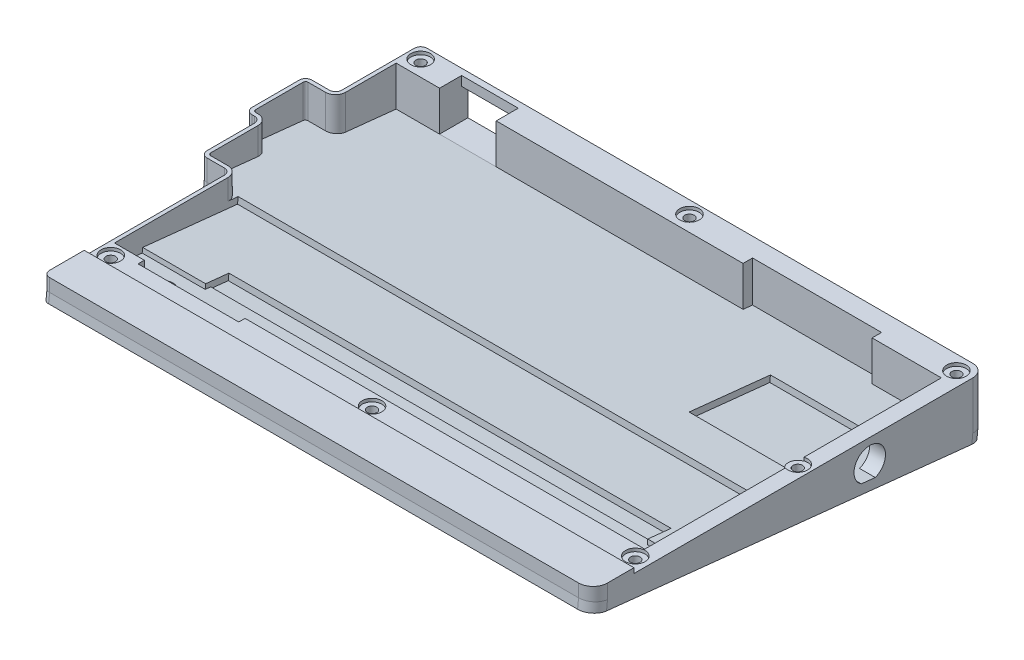
SolidWorks part; units mm, degrees
ref_plane "Front Plane" through (0, 0, 0) normal (0, 0, 1) x (1, 0, 0)
ref_plane "Top Plane" through (0, 0, 0) normal (0, 1, 0) x (1, 0, 0)
ref_plane "Right Plane" through (0, 0, 0) normal (1, 0, 0) x (0, 0, -1)
sketch "Sketch1" plane through (0, 0, 0) normal (0, 1, 0) x (1, 0, 0)
  line L0 (138.4196, 31.7518) -> (125.4196, 31.7518)
  line L1 (-35.0204, 31.7518) -> (107.4196, 31.7518)
  line L2 (140.4196, 29.7518) -> (140.4196, 6.7018)
  line L3 (-34.0204, 3.7518) -> (-34.0204, 22.7518)
  line L4 (136.4596, 27.7518) -> (136.4396, 27.7518)
  line L5 (142.4196, 4.7018) -> (147.9496, 4.7018)
  line L6 (-34.0204, 22.7518) -> (-12.0204, 22.7518)
  line L8 (149.9496, 2.7018) -> (149.9496, -12.3482)
  line L11 (147.9496, -14.3482) -> (147.1896, -14.3482)
  line L14 (145.1896, -16.3482) -> (145.1896, -31.3982)
  line L17 (143.1896, -33.3982) -> (137.6696, -33.3982)
  line L20 (135.6696, -35.3982) -> (135.6696, -77.4982)
  line L21 (-34.0204, -25.6003) -> (-34.0204, -71.4982)
  line L23 (133.6696, -79.4982) -> (-35.0204, -79.4982)
  line L28 (-39.0204, 27.7518) -> (-39.0204, 3.7518)
  line L31 (-34.0204, 3.7518) -> (-39.0204, 3.7518)
  line L32 (-34.0204, -13.4982) -> (-39.0204, -13.4982)
  line L33 (-39.0204, -75.4982) -> (-39.0204, -13.4982)
  line L34 (-34.0204, -71.4982) -> (92.9796, -71.4982)
  line L35 (92.9796, -71.4982) -> (92.9796, -73.4982)
  line L36 (92.9796, -73.4982) -> (124.9796, -73.4982)
  line L37 (124.9796, -73.4982) -> (124.9796, -71.4982)
  line L39 (134.4706, -35.3982) -> (134.4706, -71.4982)
  line L40 (134.4706, -71.4982) -> (124.9796, -71.4982)
  line L41 (137.6696, -32.1992) -> (143.1896, -32.1992)
  line L42 (-34.0204, -13.4982) -> (-34.0204, -22.1362)
  line L43 (143.9906, -31.3982) -> (143.9906, -16.3482)
  line L44 (-12.0204, 22.7518) -> (-12.0204, 25.7518)
  line L45 (147.1896, -13.1492) -> (147.9496, -13.1492)
  line L46 (148.7506, -12.3482) -> (148.7506, 2.7018)
  line L47 (-12.0204, 25.7518) -> (28.9796, 25.7518)
  line L48 (28.9796, 25.7518) -> (28.9796, 22.7518)
  line L49 (28.9796, 22.7518) -> (107.4196, 22.7518)
  line L50 (147.9496, 3.5027) -> (142.4196, 3.5027)
  line L51 (107.4196, 22.7518) -> (107.4196, 31.7518)
  line L52 (139.2206, 6.7018) -> (139.2206, 22.7518)
  line L53 (125.4196, 31.7518) -> (125.4196, 22.7518)
  line L54 (139.2206, 22.7518) -> (125.4196, 22.7518)
  arc A0 (138.4196, 31.7518) -> (140.4196, 29.7518) centre (138.4196, 29.7518) cw
  arc A1 (140.4196, 6.7018) -> (142.4196, 4.7018) centre (142.4196, 6.7018) ccw
  arc A2 (149.9496, 2.7018) -> (147.9496, 4.7018) centre (147.9496, 2.7018) ccw
  arc A3 (149.9496, -12.3482) -> (147.9496, -14.3482) centre (147.9496, -12.3482) cw
  arc A4 (147.1896, -14.3482) -> (145.1896, -16.3482) centre (147.1896, -16.3482) ccw
  arc A5 (145.1896, -31.3982) -> (143.1896, -33.3982) centre (143.1896, -31.3982) cw
  arc A6 (-35.0204, 31.7518) -> (-39.0204, 27.7518) centre (-35.0204, 27.7518) ccw
  arc A7 (-39.0204, -75.4982) -> (-35.0204, -79.4982) centre (-35.0204, -75.4982) ccw
  arc A8 (133.6696, -79.4982) -> (135.6696, -77.4982) centre (133.6696, -77.4982) ccw
  arc A9 (135.6696, -35.3982) -> (137.6696, -33.3982) centre (137.6696, -35.3982) cw
  circle A10 centre (-34.4204, 27.1518) radius 1.1
  circle A11 centre (51.0096, 27.7518) radius 1.1
  circle A12 centre (136.4396, 27.7518) radius 1.1
  circle A13 centre (-34.4204, -74.8982) radius 1.1
  circle A14 centre (48.6296, -75.4982) radius 1.1
  circle A15 centre (131.6496, -75.4982) radius 1.1
  circle A16 centre (-35.0204, -23.8682) radius 1.1
  arc A27 (-34.0204, -22.1362) -> (-34.0204, -25.6003) centre (-35.0204, -23.8682) cw
  arc A28 (139.2206, 6.7018) -> (142.4196, 3.5027) centre (142.4196, 6.7018) ccw
  arc A29 (147.9496, 3.5027) -> (148.7506, 2.7018) centre (147.9496, 2.7018) cw
  arc A30 (148.7506, -12.3482) -> (147.9496, -13.1492) centre (147.9496, -12.3482) cw
  arc A31 (147.1896, -13.1492) -> (143.9906, -16.3482) centre (147.1896, -16.3482) ccw
  arc A32 (143.9906, -31.3982) -> (143.1896, -32.1992) centre (143.1896, -31.3982) cw
  arc A33 (137.6696, -32.1992) -> (134.4706, -35.3982) centre (137.6696, -35.3982) ccw
extrude "Boss-Extrude2" add sketch "Sketch1" against normal blind 4.7 contours L41 A33 L39 L40 L37 L36 L35 L34 L21 A27 L42 L32 L33 A7 L23 A8 L20 A9 L17 A5 L14 A4 L11 A3 L8 A2 L5 A1 L2 A0 L0 L53 L54 L52 A28 L50 A29 L46 A30 L45 A31 L43 A32 A12 A13 A14 A15 | L1 A6 L28 L31 L3 L6 L44 L47 L48 L49 L51 A11 A10 region at (138.2833, 0, -29.6154) region at (31.7683, 0, -26.4895)
move or copy body "Body-Move/Copy1" bodies to move or copy 105 104 copy no rotation origin (55.4646, -2.35, 0) rotation axis (0, 0, 1) rotation angle 180
sketch "Sketch3" plane through (149.9496, 0, 0) normal (1, 0, 0) x (0, 0, -1)
  line L0 (-79.4982, 0) -> (-79.4982, -4.7) construction
  line L1 (-79.4982, 0) -> (-79.4982, -4.7)
  line L2 (31.7518, 0) -> (31.7518, -4.7) construction
  line L3 (31.7518, 0) -> (31.7518, -4.7)
  line L5 (-79.4982, -4.7) -> (31.7518, -16.3928)
  line L6 (31.7518, -16.3928) -> (31.7518, -4.7)
  line L7 (31.7518, -4.7) -> (-79.4982, -4.7)
  line M3 (-75.4982, -4.7) -> (-13.4982, -4.7)
  dimension "D1" = 6
extrude "Boss-Extrude3" add sketch "Sketch3" against normal up to surface (188.97 mm away) contours L6 L7 L5 M3 region at (149.9496, -8.5976, 5.3315) up to face at (-39.0204, -2.35, 4.8232)
sketch "Sketch4" plane through (0, -4.7, 0) normal (0, 1, 0) x (1, 0, 0)
  line L2 (145.9496, -79.4982) -> (149.9496, -79.4982)
  line L3 (149.9496, -79.4982) -> (149.9496, -75.4982)
  line L4 (-29.4904, 6.7018) -> (-29.4904, 29.7518)
  line L5 (-27.4904, 31.7518) -> (-39.0204, 31.7518)
  line L6 (-36.2604, -14.3482) -> (-37.0204, -14.3482)
  line L7 (-39.0204, -12.3482) -> (-39.0204, -79.4982)
  line L8 (-39.0204, -79.4982) -> (-22.7404, -79.4982)
  line L9 (-24.7404, -77.4982) -> (-24.7404, -35.3982)
  line L10 (-26.7404, -33.3982) -> (-32.2604, -33.3982)
  line L11 (-34.2604, -31.3982) -> (-34.2604, -16.3482)
  line L12 (-36.2604, -14.3482) -> (-37.0204, -14.3482)
  line L13 (-39.0204, -12.3482) -> (-39.0204, -79.4982)
  line L14 (-39.0204, -79.4982) -> (-22.7404, -79.4982)
  line L15 (-24.7404, -77.4982) -> (-24.7404, -35.3982)
  line L16 (-26.7404, -33.3982) -> (-32.2604, -33.3982)
  line L17 (-34.2604, -31.3982) -> (-34.2604, -16.3482)
  line L18 (-39.0204, 31.7518) -> (-39.0204, 2.7018)
  line L19 (-37.0204, 4.7018) -> (-31.4904, 4.7018)
  line L20 (-29.4904, 6.7018) -> (-29.4904, 29.7518)
  line L21 (-27.4904, 31.7518) -> (-39.0204, 31.7518)
  line L22 (-39.0204, 31.7518) -> (-39.0204, 2.7018)
  line L23 (-37.0204, 4.7018) -> (-31.4904, 4.7018)
  line L24 (145.9496, -79.4982) -> (149.9496, -79.4982)
  line L25 (149.9496, -79.4982) -> (149.9496, -75.4982)
  line L26 (149.9496, 31.7518) -> (145.9496, 31.7518)
  line L27 (149.9496, 27.7518) -> (149.9496, 31.7518)
  line L28 (149.9496, 31.7518) -> (145.9496, 31.7518)
  line L29 (149.9496, 27.7518) -> (149.9496, 31.7518)
  arc A1 (145.9496, -79.4982) -> (149.9496, -75.4982) centre (145.9496, -75.4982) ccw
  arc A2 (145.9496, -79.4982) -> (149.9496, -75.4982) centre (145.9496, -75.4982) ccw
  arc A3 (-27.4904, 31.7518) -> (-29.4904, 29.7518) centre (-27.4904, 29.7518) ccw
  arc A4 (-37.0204, 4.7018) -> (-39.0204, 2.7018) centre (-37.0204, 2.7018) ccw
  arc A5 (-39.0204, -12.3482) -> (-37.0204, -14.3482) centre (-37.0204, -12.3482) ccw
  arc A6 (-24.7404, -77.4982) -> (-22.7404, -79.4982) centre (-22.7404, -77.4982) ccw
  arc A7 (-24.7404, -35.3982) -> (-26.7404, -33.3982) centre (-26.7404, -35.3982) ccw
  arc A8 (-34.2604, -31.3982) -> (-32.2604, -33.3982) centre (-32.2604, -31.3982) ccw
  arc A9 (-34.2604, -16.3482) -> (-36.2604, -14.3482) centre (-36.2604, -16.3482) ccw
  arc A10 (-39.0204, -12.3482) -> (-37.0204, -14.3482) centre (-37.0204, -12.3482) ccw
  arc A11 (-24.7404, -77.4982) -> (-22.7404, -79.4982) centre (-22.7404, -77.4982) ccw
  arc A12 (-24.7404, -35.3982) -> (-26.7404, -33.3982) centre (-26.7404, -35.3982) ccw
  arc A13 (-34.2604, -31.3982) -> (-32.2604, -33.3982) centre (-32.2604, -31.3982) ccw
  arc A14 (-34.2604, -16.3482) -> (-36.2604, -14.3482) centre (-36.2604, -16.3482) ccw
  arc A15 (-31.4904, 4.7018) -> (-29.4904, 6.7018) centre (-31.4904, 6.7018) ccw
  arc A16 (-27.4904, 31.7518) -> (-29.4904, 29.7518) centre (-27.4904, 29.7518) ccw
  arc A17 (-37.0204, 4.7018) -> (-39.0204, 2.7018) centre (-37.0204, 2.7018) ccw
  arc A18 (-31.4904, 4.7018) -> (-29.4904, 6.7018) centre (-31.4904, 6.7018) ccw
  arc A19 (149.9496, 27.7518) -> (145.9496, 31.7518) centre (145.9496, 27.7518) ccw
  arc A20 (149.9496, 27.7518) -> (145.9496, 31.7518) centre (145.9496, 27.7518) ccw
  dimension "D1" = 0
  dimension "D2" = 0
  dimension "D3" = 0
  dimension "D4" = 0
extrude "Cut-Extrude1" cut sketch "Sketch4" against normal through all
ref_plane "Plane4" through (0, 15, 0) normal (0, 1, 0) x (1, 0, 0)
sketch "Sketch10" plane through (0, 15, 0) normal (0, 1, 0) x (1, 0, 0)
  line L0 (-14.4904, 22.7518) -> (3.5096, 22.7518)
  line L1 (144.9496, 3.7518) -> (144.9496, -13.4982)
  line L27 (-14.4904, 31.7518) -> (-14.4904, 22.7518)
  line L28 (-14.4904, 22.7518) -> (-28.2913, 22.7518)
  line L29 (-28.2913, 22.7518) -> (-28.2913, 6.7018)
  line L30 (-31.4904, 3.5027) -> (-37.0204, 3.5027)
  line L31 (-37.8213, 2.7018) -> (-37.8213, -12.3482)
  line L32 (-37.0204, -13.1492) -> (-36.2604, -13.1492)
  line L33 (-33.0613, -16.3482) -> (-33.0613, -31.3982)
  line L34 (-32.2604, -32.1992) -> (-26.7404, -32.1992)
  line L35 (-23.5413, -35.3982) -> (-23.5413, -71.4982)
  line L36 (-23.5413, -71.4982) -> (-14.0504, -71.4982)
  line L37 (-14.0504, -71.4982) -> (-14.0504, -73.4982)
  line L38 (-14.0504, -73.4982) -> (17.9496, -73.4982)
  line L39 (17.9496, -73.4982) -> (17.9496, -71.4982)
  line L40 (17.9496, -71.4982) -> (144.9496, -71.4982)
  line L41 (144.9496, -71.4982) -> (144.9496, -25.6003)
  line L42 (144.9496, -22.1362) -> (144.9496, -13.4982)
  line L43 (144.9496, -13.4982) -> (149.9496, -13.4982)
  line L44 (149.9496, -13.4982) -> (149.9496, 3.7518)
  line L45 (149.9496, 3.7518) -> (144.9496, 3.7518)
  line L46 (144.9496, 3.7518) -> (144.9496, 22.7518)
  line L47 (144.9496, 22.7518) -> (122.9496, 22.7518)
  line L48 (122.9496, 22.7518) -> (122.9496, 25.7518)
  line L49 (122.9496, 25.7518) -> (81.9496, 25.7518)
  line L50 (81.9496, 25.7518) -> (81.9496, 22.7518)
  line L51 (81.9496, 22.7518) -> (3.5096, 22.7518)
  line L52 (3.5096, 22.7518) -> (3.5096, 31.7518)
  line L53 (3.5096, 31.7518) -> (-14.4904, 31.7518)
  line L54 (-14.4904, 31.7518) -> (-14.4904, 22.7518)
  line L55 (-14.4904, 22.7518) -> (-28.2913, 22.7518)
  line L56 (-28.2913, 22.7518) -> (-28.2913, 6.7018)
  line L57 (-31.4904, 3.5027) -> (-37.0204, 3.5027)
  line L58 (-37.8213, 2.7018) -> (-37.8213, -12.3482)
  line L59 (-37.0204, -13.1492) -> (-36.2604, -13.1492)
  line L60 (-33.0613, -16.3482) -> (-33.0613, -31.3982)
  line L61 (-32.2604, -32.1992) -> (-26.7404, -32.1992)
  line L62 (-23.5413, -35.3982) -> (-23.5413, -71.4982)
  line L63 (-23.5413, -71.4982) -> (-14.0504, -71.4982)
  line L64 (-14.0504, -71.4982) -> (-14.0504, -73.4982)
  line L65 (-14.0504, -73.4982) -> (17.9496, -73.4982)
  line L66 (17.9496, -73.4982) -> (17.9496, -71.4982)
  line L67 (17.9496, -71.4982) -> (144.9496, -71.4982)
  line L68 (144.9496, -71.4982) -> (144.9496, -25.6003)
  line L69 (144.9496, -22.1362) -> (144.9496, -13.4982)
  line L70 (144.9496, -13.4982) -> (149.9496, -13.4982)
  line L71 (149.9496, -13.4982) -> (149.9496, 3.7518)
  line L72 (149.9496, 3.7518) -> (144.9496, 3.7518)
  line L73 (144.9496, 3.7518) -> (144.9496, 22.7518)
  line L74 (144.9496, 22.7518) -> (122.9496, 22.7518)
  line L75 (122.9496, 22.7518) -> (122.9496, 25.7518)
  line L76 (122.9496, 25.7518) -> (81.9496, 25.7518)
  line L77 (81.9496, 25.7518) -> (81.9496, 22.7518)
  line L78 (81.9496, 22.7518) -> (3.5096, 22.7518)
  line L79 (3.5096, 22.7518) -> (3.5096, 31.7518)
  line L80 (3.5096, 31.7518) -> (-14.4904, 31.7518)
  arc A7 (-31.4904, 3.5027) -> (-28.2913, 6.7018) centre (-31.4904, 6.7018) ccw
  arc A8 (-37.0204, 3.5027) -> (-37.8213, 2.7018) centre (-37.0204, 2.7018) ccw
  arc A9 (-37.8213, -12.3482) -> (-37.0204, -13.1492) centre (-37.0204, -12.3482) ccw
  arc A10 (-33.0613, -16.3482) -> (-36.2604, -13.1492) centre (-36.2604, -16.3482) ccw
  arc A11 (-33.0613, -31.3982) -> (-32.2604, -32.1992) centre (-32.2604, -31.3982) ccw
  arc A12 (-23.5413, -35.3982) -> (-26.7404, -32.1992) centre (-26.7404, -35.3982) ccw
  arc A13 (144.9496, -22.1362) -> (144.9496, -25.6003) centre (145.9496, -23.8682) ccw
  arc A14 (-31.4904, 3.5027) -> (-28.2913, 6.7018) centre (-31.4904, 6.7018) ccw
  arc A15 (-37.0204, 3.5027) -> (-37.8213, 2.7018) centre (-37.0204, 2.7018) ccw
  arc A16 (-37.8213, -12.3482) -> (-37.0204, -13.1492) centre (-37.0204, -12.3482) ccw
  arc A17 (-33.0613, -16.3482) -> (-36.2604, -13.1492) centre (-36.2604, -16.3482) ccw
  arc A18 (-33.0613, -31.3982) -> (-32.2604, -32.1992) centre (-32.2604, -31.3982) ccw
  arc A19 (-23.5413, -35.3982) -> (-26.7404, -32.1992) centre (-26.7404, -35.3982) ccw
  arc A20 (144.9496, -22.1362) -> (144.9496, -25.6003) centre (145.9496, -23.8682) ccw
  dimension "D1" = 0
extrude "Cut-Extrude2" cut sketch "Sketch10" against normal through all contours A20 L69 L1 L73 L74 L75 L76 L77 L78 L0 L55 L56 A14 L57 A15 L58 A16 L59 A17 L60 A18 L61 A19 L62 L63 L64 L65 L66 L67 L68 region at (57.9798, 15, 23.6888)
sketch "Sketch11" plane through (144.9496, 0, 0) normal (-1, 0, 0) x (0, 0, 1)
  line L0 (-22.7518, -15.4469) -> (71.4982, -5.5408)
  line L1 (71.4982, -5.5408) -> (71.4982, -3.5408)
  line L2 (71.4982, 0) -> (71.4982, -5.5408) construction
  line L3 (71.4982, -3.5408) -> (-22.7518, -13.4469)
  line L4 (-22.7518, 0) -> (-22.7518, -15.4469) construction
  line L5 (-22.7518, -13.4469) -> (-22.7518, -15.4469)
  dimension "D1" = 2
  dimension "D2" = 2
extrude "Boss-Extrude4" add sketch "Sketch11" along normal up to surface (182.7709 mm away)
sketch "Sketch12" plane through (0, -10.9348, 1.1493) normal (0, 0.9945, -0.1045) x (1, 0, 0)
  line L0 (-29.4904, 7.8943) -> (-29.4904, 24.0327) construction
  line L1 (-29.4904, 24.0327) -> (-37.8213, 24.0327) construction
  line L2 (-37.8213, 24.0327) -> (-37.8213, 5.715) construction
  line L3 (-37.0204, 5.8833) -> (-31.4904, 5.8833) construction
  line L4 (-36.2604, -13.2716) -> (-37.0204, -13.2716) construction
  line L5 (-37.8213, -13.1033) -> (-37.8213, -70.7364) construction
  line L6 (-37.8213, -70.7364) -> (-24.7404, -70.7364) construction
  line L7 (-24.7404, -70.7364) -> (-24.7404, -34.4376) construction
  line L8 (-26.7404, -32.4266) -> (-32.2604, -32.4266) construction
  line L9 (-34.2604, -30.4155) -> (-34.2604, -15.2826) construction
  line L10 (-29.4904, 7.8943) -> (-29.4904, 24.0327)
  line L11 (-29.4904, 24.0327) -> (-37.8213, 24.0327)
  line L12 (-37.8213, 24.0327) -> (-37.8213, 5.715)
  line L13 (-37.0204, 5.8833) -> (-31.4904, 5.8833)
  line L14 (-36.2604, -13.2716) -> (-37.0204, -13.2716)
  line L15 (-37.8213, -13.1033) -> (-37.8213, -70.7364)
  line L16 (-37.8213, -70.7364) -> (-24.7404, -70.7364)
  line L17 (-24.7404, -70.7364) -> (-24.7404, -34.4376)
  line L18 (-26.7404, -32.4266) -> (-32.2604, -32.4266)
  line L19 (-34.2604, -30.4155) -> (-34.2604, -15.2826)
  line L20 (-37.8213, 24.0327) -> (-37.8213, 25.9101)
  line L21 (-29.4904, 24.0327) -> (-29.4904, 27.1127)
  line L22 (-29.4904, 27.1127) -> (-37.8213, 25.9101)
  ellipse E0 centre (-31.4904, 7.8943) end of major axis (-31.4904, 9.9053) minor radius 2 (-31.4904, 5.8833) -> (-29.4904, 7.8943) ccw construction
  ellipse E1 centre (-37.0204, 3.8723) end of major axis (-37.0204, 5.8833) minor radius 2 (-37.0204, 5.8833) -> (-37.8213, 5.715) ccw construction
  ellipse E2 centre (-37.0204, -11.2606) end of major axis (-37.0204, -9.2496) minor radius 2 (-37.8213, -13.1033) -> (-37.0204, -13.2716) ccw construction
  ellipse E3 centre (-26.7404, -34.4376) end of major axis (-26.7404, -32.4266) minor radius 2 (-24.7404, -34.4376) -> (-26.7404, -32.4266) ccw construction
  ellipse E4 centre (-32.2604, -30.4155) end of major axis (-32.2604, -28.4045) minor radius 2 (-34.2604, -30.4155) -> (-32.2604, -32.4266) ccw construction
  ellipse E5 centre (-36.2604, -15.2826) end of major axis (-36.2604, -13.2716) minor radius 2 (-34.2604, -15.2826) -> (-36.2604, -13.2716) ccw construction
  ellipse E6 centre (-31.4904, 7.8943) end of major axis (-31.4904, 9.9053) minor radius 2 (-31.4904, 5.8833) -> (-29.4904, 7.8943) ccw
  ellipse E7 centre (-37.0204, 3.8723) end of major axis (-37.0204, 5.8833) minor radius 2 (-37.0204, 5.8833) -> (-37.8213, 5.715) ccw
  ellipse E8 centre (-37.0204, -11.2606) end of major axis (-37.0204, -9.2496) minor radius 2 (-37.8213, -13.1033) -> (-37.0204, -13.2716) ccw
  ellipse E9 centre (-26.7404, -34.4376) end of major axis (-26.7404, -32.4266) minor radius 2 (-24.7404, -34.4376) -> (-26.7404, -32.4266) ccw
  ellipse E10 centre (-32.2604, -30.4155) end of major axis (-32.2604, -28.4045) minor radius 2 (-34.2604, -30.4155) -> (-32.2604, -32.4266) ccw
  ellipse E11 centre (-36.2604, -15.2826) end of major axis (-36.2604, -13.2716) minor radius 2 (-34.2604, -15.2826) -> (-36.2604, -13.2716) ccw
sketch "Sketch26" plane through (-37.8213, 0, 0) normal (-1, 0, 0) x (0, 0, 1)
  line L0 (14.1808, -9.5651) -> (-4.5344, -11.5322)
  line L1 (-4.5344, -13.5322) -> (14.1808, -11.5651)
  line L4 (-22.7518, -15.4469) -> (-4.5344, -13.5322)
  line L5 (-4.5344, -13.5322) -> (-4.5344, -11.5322)
  line L6 (-4.5344, -11.5322) -> (-22.7518, -13.4469)
  line L7 (-22.7518, -13.4469) -> (-22.7518, -15.4469)
  line L8 (-22.7518, -15.4469) -> (-4.5344, -13.5322)
  line L9 (-4.5344, -13.5322) -> (-4.5344, -11.5322)
  line L10 (-4.5344, -11.5322) -> (-22.7518, -13.4469)
  line L11 (-22.7518, -13.4469) -> (-22.7518, -15.4469)
  line L12 (14.1808, -9.5651) -> (14.1808, -11.5651)
  line L13 (14.1808, -11.5651) -> (71.4982, -5.5408)
  line L14 (71.4982, -5.5408) -> (71.4982, -3.5408)
  line L15 (71.4982, -3.5408) -> (14.1808, -9.5651)
  line L16 (14.1808, -9.5651) -> (14.1808, -11.5651)
  line L17 (14.1808, -11.5651) -> (71.4982, -5.5408)
  line L18 (71.4982, -5.5408) -> (71.4982, -3.5408)
  line L19 (71.4982, -3.5408) -> (14.1808, -9.5651)
  line M9 (14.1808, -9.5651) -> (14.1808, -11.5651)
  line M10 (14.1808, -11.5651) -> (71.4982, -5.5408)
  line M11 (71.4982, -5.5408) -> (71.4982, -3.5408)
  line M12 (71.4982, -3.5408) -> (14.1808, -9.5651)
  dimension "D1" = 0
  dimension "D2" = 0
extrude "Boss-Extrude10" add sketch "Sketch26" along normal blind 11 contours L10 L11 L8 L9 | L9 L1 L0 M9 | M12 M9 M10 M11 region at (-37.8213, -11.5487, 4.8232) region at (-37.8213, -7.553, 42.8395) region at (-37.8213, -13.4895, -13.6431)
sketch "Sketch28" plane through (0, -10.9348, 1.1493) normal (0, 0.9945, -0.1045) x (1, 0, 0)
  line L0 (-48.8213, 24.0327) -> (-52.7132, 28.3929)
  line L1 (-52.7132, 28.3929) -> (-29.4904, 30.8021)
  line L2 (-29.4904, 30.8021) -> (-29.4904, 24.0327)
  line L10 (-29.4904, 7.8943) -> (-29.4904, 24.0327)
  line L11 (-29.4904, 24.0327) -> (-48.8213, 24.0327)
  line L12 (-48.8213, 24.0327) -> (-48.8213, -70.7364)
  line L13 (-48.8213, -70.7364) -> (-24.7404, -70.7364)
  line L14 (-24.7404, -70.7364) -> (-24.7404, -34.4376)
  line L15 (-26.7404, -32.4266) -> (-32.2604, -32.4266)
  line L16 (-34.2604, -30.4155) -> (-34.2604, -15.2826)
  line L17 (-36.2604, -13.2716) -> (-37.0204, -13.2716)
  line L18 (-39.0204, -11.2606) -> (-39.0204, 3.8723)
  line L19 (-37.0204, 5.8833) -> (-31.4904, 5.8833)
  line L20 (-29.4904, 7.8943) -> (-29.4904, 24.0327)
  line L21 (-29.4904, 24.0327) -> (-48.8213, 24.0327)
  line L22 (-48.8213, 24.0327) -> (-48.8213, -70.7364)
  line L23 (-48.8213, -70.7364) -> (-24.7404, -70.7364)
  line L24 (-24.7404, -70.7364) -> (-24.7404, -34.4376)
  line L25 (-26.7404, -32.4266) -> (-32.2604, -32.4266)
  line L26 (-34.2604, -30.4155) -> (-34.2604, -15.2826)
  line L27 (-36.2604, -13.2716) -> (-37.0204, -13.2716)
  line L28 (-39.0204, -11.2606) -> (-39.0204, 3.8723)
  line L29 (-37.0204, 5.8833) -> (-31.4904, 5.8833)
  ellipse E6 centre (-31.4904, 7.8943) end of major axis (-31.4904, 9.9053) minor radius 2 (-31.4904, 5.8833) -> (-29.4904, 7.8943) ccw
  ellipse E7 centre (-26.7404, -34.4376) end of major axis (-26.7404, -32.4266) minor radius 2 (-24.7404, -34.4376) -> (-26.7404, -32.4266) ccw
  ellipse E8 centre (-32.2604, -30.4155) end of major axis (-32.2604, -28.4045) minor radius 2 (-34.2604, -30.4155) -> (-32.2604, -32.4266) ccw
  ellipse E9 centre (-36.2604, -15.2826) end of major axis (-36.2604, -13.2716) minor radius 2 (-34.2604, -15.2826) -> (-36.2604, -13.2716) ccw
  ellipse E10 centre (-37.0204, -11.2606) end of major axis (-37.0204, -9.2496) minor radius 2 (-39.0204, -11.2606) -> (-37.0204, -13.2716) ccw
  ellipse E11 centre (-37.0204, 3.8723) end of major axis (-37.0204, 5.8833) minor radius 2 (-37.0204, 5.8833) -> (-39.0204, 3.8723) ccw
  ellipse E12 centre (-31.4904, 7.8943) end of major axis (-31.4904, 9.9053) minor radius 2 (-31.4904, 5.8833) -> (-29.4904, 7.8943) ccw
  ellipse E13 centre (-26.7404, -34.4376) end of major axis (-26.7404, -32.4266) minor radius 2 (-24.7404, -34.4376) -> (-26.7404, -32.4266) ccw
  ellipse E14 centre (-32.2604, -30.4155) end of major axis (-32.2604, -28.4045) minor radius 2 (-34.2604, -30.4155) -> (-32.2604, -32.4266) ccw
  ellipse E15 centre (-36.2604, -15.2826) end of major axis (-36.2604, -13.2716) minor radius 2 (-34.2604, -15.2826) -> (-36.2604, -13.2716) ccw
  ellipse E16 centre (-37.0204, -11.2606) end of major axis (-37.0204, -9.2496) minor radius 2 (-39.0204, -11.2606) -> (-37.0204, -13.2716) ccw
  ellipse E17 centre (-37.0204, 3.8723) end of major axis (-37.0204, 5.8833) minor radius 2 (-37.0204, 5.8833) -> (-39.0204, 3.8723) ccw
  ellipse M17 centre (-31.4904, 7.8943) end of major axis (-31.4904, 9.9053) minor radius 2 (-31.4904, 5.8833) -> (-29.4904, 7.8943) ccw
  line M18 (-29.4904, 7.8943) -> (-29.4904, 24.0327)
  line M19 (-29.4904, 24.0327) -> (-48.8213, 24.0327)
  line M20 (-48.8213, 24.0327) -> (-48.8213, -70.7364)
  line M21 (-48.8213, -70.7364) -> (-24.7404, -70.7364)
  line M22 (-24.7404, -70.7364) -> (-24.7404, -34.4376)
  ellipse M23 centre (-26.7404, -34.4376) end of major axis (-26.7404, -32.4266) minor radius 2 (-24.7404, -34.4376) -> (-26.7404, -32.4266) ccw
  line M24 (-26.7404, -32.4266) -> (-32.2604, -32.4266)
  ellipse M25 centre (-32.2604, -30.4155) end of major axis (-32.2604, -28.4045) minor radius 2 (-32.2604, -32.4266) -> (-34.2604, -30.4155) cw
  line M26 (-34.2604, -30.4155) -> (-34.2604, -15.2826)
  ellipse M27 centre (-36.2604, -15.2826) end of major axis (-36.2604, -13.2716) minor radius 2 (-34.2604, -15.2826) -> (-36.2604, -13.2716) ccw
  line M28 (-36.2604, -13.2716) -> (-37.0204, -13.2716)
  ellipse M29 centre (-37.0204, -11.2606) end of major axis (-37.0204, -9.2496) minor radius 2 (-37.0204, -13.2716) -> (-39.0204, -11.2606) cw
  line M30 (-39.0204, -11.2606) -> (-39.0204, 3.8723)
  ellipse M31 centre (-37.0204, 3.8723) end of major axis (-37.0204, 5.8833) minor radius 2 (-39.0204, 3.8723) -> (-37.0204, 5.8833) cw
  line M32 (-37.0204, 5.8833) -> (-31.4904, 5.8833)
  dimension "D1" = 0
extrude "Cut-Extrude8" cut sketch "Sketch28" against normal blind 11 contours M32 M17 M18 M19 M20 M21 M22 M23 M24 M25 M26 M27 M28 M29 M30 M31 | L2 L1 L0 M19 region at (-39.4803, -13.7524, -25.6581) region at (-38.8035, -7.967, 29.3861)
sketch "Sketch30" plane through (122.9496, 0, 0) normal (-1, 0, 0) x (0, 0, 1)
  line L0 (-25.7518, -15.7622) -> (-22.7518, -15.4469)
  line L1 (-22.7518, -15.4469) -> (-22.7518, -13.4469)
  line L2 (-22.7518, -15.4469) -> (-22.7518, -13.4469) construction
  line L3 (-22.7518, -13.4469) -> (-25.7518, -13.7622)
  line L4 (-25.7518, 0) -> (-25.7518, -15.7622) construction
  line L5 (-25.7518, -13.7622) -> (-25.7518, -15.7622)
extrude "Boss-Extrude11" add sketch "Sketch30" along normal up to surface (41 mm away)
sketch "Sketch32" plane through (17.9496, 0, 0) normal (-1, 0, 0) x (0, 0, 1)
  line L0 (73.4982, -5.3306) -> (71.4982, -5.5408)
  line L1 (71.4982, -5.5408) -> (71.4982, -3.5408)
  line L2 (71.4982, -3.5408) -> (73.4982, -3.3306)
  line L3 (73.4982, 0) -> (73.4982, -5.3306) construction
  line L4 (73.4982, -3.3306) -> (73.4982, -5.3306)
  dimension "D1" = 2
extrude "Boss-Extrude14" add sketch "Sketch32" along normal up to surface (32 mm away)
sketch "Sketch35" plane through (0, 0, 0) normal (0, 1, 0) x (1, 0, 0)
  line L0 (149.9496, 3.7518) -> (149.9496, -13.4982)
  line L1 (149.9496, -13.4982) -> (144.9496, -13.4982)
  line L2 (144.9496, -13.4982) -> (144.9496, 3.7518)
  line L3 (144.9496, 3.7518) -> (149.9496, 3.7518)
ref_plane "Plane5" through (149.9496, -5.1204, 75.4982) normal (0, -1, 0) x (-1, 0, 0)
sketch "Sketch47" plane through (0, 0, 0) normal (0, 1, 0) x (1, 0, 0)
  circle A0 centre (145.3496, -74.8982) radius 3.1
  circle A1 centre (62.2996, -75.4982) radius 3.1
  circle A2 centre (-20.7204, -75.4982) radius 3.1
  circle A3 centre (-25.5104, 27.7518) radius 3.1
  circle A4 centre (59.9196, 27.7518) radius 3.1
  circle A5 centre (145.3496, 27.1518) radius 3.1
  circle A6 centre (145.9496, -23.8682) radius 3.1
extrude "Cut-Extrude17" cut sketch "Sketch47" against normal blind 1.8
sketch "Sketch48" plane through (0, 0, 0) normal (0, 1, 0) x (1, 0, 0)
  line L10 (145.9496, 31.7518) -> (3.5096, 31.7518)
  line L11 (3.5096, 31.7518) -> (3.5096, 22.7518)
  line L12 (3.5096, 22.7518) -> (81.9496, 22.7518)
  line L13 (81.9496, 22.7518) -> (81.9496, 25.7518)
  line L14 (81.9496, 25.7518) -> (122.9496, 25.7518)
  line L15 (122.9496, 25.7518) -> (122.9496, 22.7518)
  line L16 (122.9496, 22.7518) -> (144.9496, 22.7518)
  line L17 (144.9496, 22.7518) -> (144.9496, 3.7518)
  line L18 (144.9496, 3.7518) -> (149.9496, 3.7518)
  line L19 (149.9496, 3.7518) -> (149.9496, 27.7518)
  line L20 (145.9496, 31.7518) -> (3.5096, 31.7518)
  line L21 (3.5096, 31.7518) -> (3.5096, 22.7518)
  line L22 (3.5096, 22.7518) -> (81.9496, 22.7518)
  line L23 (81.9496, 22.7518) -> (81.9496, 25.7518)
  line L24 (81.9496, 25.7518) -> (122.9496, 25.7518)
  line L25 (122.9496, 25.7518) -> (122.9496, 22.7518)
  line L26 (122.9496, 22.7518) -> (144.9496, 22.7518)
  line L27 (144.9496, 22.7518) -> (144.9496, 3.7518)
  line L28 (144.9496, 3.7518) -> (149.9496, 3.7518)
  line L29 (149.9496, 3.7518) -> (149.9496, 27.7518)
  line L47 (144.9496, -13.4982) -> (144.9496, -20.9339)
  line L48 (144.9496, -26.8025) -> (144.9496, -71.4982)
  line L49 (144.9496, -71.4982) -> (17.9496, -71.4982)
  line L50 (17.9496, -71.4982) -> (17.9496, -73.4982)
  line L51 (17.9496, -73.4982) -> (-14.0504, -73.4982)
  line L52 (-14.0504, -73.4982) -> (-14.0504, -71.4982)
  line L53 (-14.0504, -71.4982) -> (-23.5413, -71.4982)
  line L54 (-23.5413, -71.4982) -> (-23.5413, -35.3982)
  line L55 (-26.7404, -32.1992) -> (-32.2604, -32.1992)
  line L56 (-33.0613, -31.3982) -> (-33.0613, -16.3482)
  line L57 (-36.2604, -13.1492) -> (-37.0204, -13.1492)
  line L58 (-37.8213, -12.3482) -> (-37.8213, 2.7018)
  line L59 (-37.0204, 3.5027) -> (-31.4904, 3.5027)
  line L60 (-28.2913, 6.7018) -> (-28.2913, 22.7518)
  line L61 (-28.2913, 22.7518) -> (-14.4904, 22.7518)
  line L62 (-14.4904, 22.7518) -> (-14.4904, 31.7518)
  line L63 (-14.4904, 31.7518) -> (-27.4904, 31.7518)
  line L64 (-29.4904, 29.7518) -> (-29.4904, 6.7018)
  line L65 (-31.4904, 4.7018) -> (-37.0204, 4.7018)
  line L66 (-39.0204, 2.7018) -> (-39.0204, -12.3482)
  line L67 (-37.0204, -14.3482) -> (-36.2604, -14.3482)
  line L68 (-34.2604, -16.3482) -> (-34.2604, -31.3982)
  line L69 (-32.2604, -33.3982) -> (-26.7404, -33.3982)
  line L70 (-24.7404, -35.3982) -> (-24.7404, -77.4982)
  line L71 (-22.7404, -79.4982) -> (145.9496, -79.4982)
  line L72 (149.9496, -75.4982) -> (149.9496, -13.4982)
  line L73 (149.9496, -13.4982) -> (144.9496, -13.4982)
  line L74 (144.9496, -13.4982) -> (144.9496, -20.9339)
  line L75 (144.9496, -26.8025) -> (144.9496, -71.4982)
  line L76 (144.9496, -71.4982) -> (17.9496, -71.4982)
  line L77 (17.9496, -71.4982) -> (17.9496, -73.4982)
  line L78 (17.9496, -73.4982) -> (-14.0504, -73.4982)
  line L79 (-14.0504, -73.4982) -> (-14.0504, -71.4982)
  line L80 (-14.0504, -71.4982) -> (-23.5413, -71.4982)
  line L81 (-23.5413, -71.4982) -> (-23.5413, -35.3982)
  line L82 (-26.7404, -32.1992) -> (-32.2604, -32.1992)
  line L83 (-33.0613, -31.3982) -> (-33.0613, -16.3482)
  line L84 (-36.2604, -13.1492) -> (-37.0204, -13.1492)
  line L85 (-37.8213, -12.3482) -> (-37.8213, 2.7018)
  line L86 (-37.0204, 3.5027) -> (-31.4904, 3.5027)
  line L87 (-28.2913, 6.7018) -> (-28.2913, 22.7518)
  line L88 (-28.2913, 22.7518) -> (-14.4904, 22.7518)
  line L89 (-14.4904, 22.7518) -> (-14.4904, 31.7518)
  line L90 (-14.4904, 31.7518) -> (-27.4904, 31.7518)
  line L91 (-29.4904, 29.7518) -> (-29.4904, 6.7018)
  line L92 (-31.4904, 4.7018) -> (-37.0204, 4.7018)
  line L93 (-39.0204, 2.7018) -> (-39.0204, -12.3482)
  line L94 (-37.0204, -14.3482) -> (-36.2604, -14.3482)
  line L95 (-34.2604, -16.3482) -> (-34.2604, -31.3982)
  line L96 (-32.2604, -33.3982) -> (-26.7404, -33.3982)
  line L97 (-24.7404, -35.3982) -> (-24.7404, -77.4982)
  line L98 (-22.7404, -79.4982) -> (145.9496, -79.4982)
  line L99 (149.9496, -75.4982) -> (149.9496, -13.4982)
  line L100 (149.9496, -13.4982) -> (144.9496, -13.4982)
  arc A1 (149.9496, 27.7518) -> (145.9496, 31.7518) centre (145.9496, 27.7518) ccw
  arc A2 (149.9496, 27.7518) -> (145.9496, 31.7518) centre (145.9496, 27.7518) ccw
  arc A18 (144.9496, -26.8025) -> (144.9496, -20.9339) centre (145.9496, -23.8682) ccw
  arc A19 (-23.5413, -35.3982) -> (-26.7404, -32.1992) centre (-26.7404, -35.3982) ccw
  arc A20 (-33.0613, -31.3982) -> (-32.2604, -32.1992) centre (-32.2604, -31.3982) ccw
  arc A21 (-33.0613, -16.3482) -> (-36.2604, -13.1492) centre (-36.2604, -16.3482) ccw
  arc A22 (-37.8213, -12.3482) -> (-37.0204, -13.1492) centre (-37.0204, -12.3482) ccw
  arc A23 (-37.0204, 3.5027) -> (-37.8213, 2.7018) centre (-37.0204, 2.7018) ccw
  arc A24 (-31.4904, 3.5027) -> (-28.2913, 6.7018) centre (-31.4904, 6.7018) ccw
  arc A25 (-27.4904, 31.7518) -> (-29.4904, 29.7518) centre (-27.4904, 29.7518) ccw
  arc A26 (-31.4904, 4.7018) -> (-29.4904, 6.7018) centre (-31.4904, 6.7018) ccw
  arc A27 (-37.0204, 4.7018) -> (-39.0204, 2.7018) centre (-37.0204, 2.7018) ccw
  arc A28 (-39.0204, -12.3482) -> (-37.0204, -14.3482) centre (-37.0204, -12.3482) ccw
  arc A29 (-34.2604, -16.3482) -> (-36.2604, -14.3482) centre (-36.2604, -16.3482) ccw
  arc A30 (-34.2604, -31.3982) -> (-32.2604, -33.3982) centre (-32.2604, -31.3982) ccw
  arc A31 (-24.7404, -35.3982) -> (-26.7404, -33.3982) centre (-26.7404, -35.3982) ccw
  arc A32 (-24.7404, -77.4982) -> (-22.7404, -79.4982) centre (-22.7404, -77.4982) ccw
  arc A33 (145.9496, -79.4982) -> (149.9496, -75.4982) centre (145.9496, -75.4982) ccw
  arc A34 (144.9496, -26.8025) -> (144.9496, -20.9339) centre (145.9496, -23.8682) ccw
  arc A35 (-23.5413, -35.3982) -> (-26.7404, -32.1992) centre (-26.7404, -35.3982) ccw
  arc A36 (-33.0613, -31.3982) -> (-32.2604, -32.1992) centre (-32.2604, -31.3982) ccw
  arc A37 (-33.0613, -16.3482) -> (-36.2604, -13.1492) centre (-36.2604, -16.3482) ccw
  arc A38 (-37.8213, -12.3482) -> (-37.0204, -13.1492) centre (-37.0204, -12.3482) ccw
  arc A39 (-37.0204, 3.5027) -> (-37.8213, 2.7018) centre (-37.0204, 2.7018) ccw
  arc A40 (-31.4904, 3.5027) -> (-28.2913, 6.7018) centre (-31.4904, 6.7018) ccw
  arc A41 (-27.4904, 31.7518) -> (-29.4904, 29.7518) centre (-27.4904, 29.7518) ccw
  arc A42 (-31.4904, 4.7018) -> (-29.4904, 6.7018) centre (-31.4904, 6.7018) ccw
  arc A43 (-37.0204, 4.7018) -> (-39.0204, 2.7018) centre (-37.0204, 2.7018) ccw
  arc A44 (-39.0204, -12.3482) -> (-37.0204, -14.3482) centre (-37.0204, -12.3482) ccw
  arc A45 (-34.2604, -16.3482) -> (-36.2604, -14.3482) centre (-36.2604, -16.3482) ccw
  arc A46 (-34.2604, -31.3982) -> (-32.2604, -33.3982) centre (-32.2604, -31.3982) ccw
  arc A47 (-24.7404, -35.3982) -> (-26.7404, -33.3982) centre (-26.7404, -35.3982) ccw
  arc A48 (-24.7404, -77.4982) -> (-22.7404, -79.4982) centre (-22.7404, -77.4982) ccw
  arc A49 (145.9496, -79.4982) -> (149.9496, -75.4982) centre (145.9496, -75.4982) ccw
  dimension "D1" = 0
  dimension "D2" = 0
extrude "Cut-Extrude18" cut sketch "Sketch48" against normal blind 0.8
sketch "Sketch49" plane through (0, -12.913, 1.3572) normal (0, -0.9945, 0.1045) x (1, 0, 0)
  line L0 (17.9496, 70.7364) -> (144.9496, 70.7364) construction
  line L1 (17.9496, 70.7364) -> (144.9496, 70.7364)
  line L2 (-23.5413, 46.5714) -> (-23.5413, 70.7364)
  line L6 (144.9496, 46.5714) -> (144.9496, 70.7364)
  line L9 (17.9496, 70.7364) -> (-23.5413, 70.7364)
  line L10 (144.9496, 46.5714) -> (-23.5413, 46.5714)
extrude "Cut-Extrude19" cut sketch "Sketch49" against normal blind 10
sketch "Sketch50" plane through (0, -12.913, 1.3572) normal (0, -0.9945, 0.1045) x (1, 0, 0)
  line L5 (105.9496, 17.3552) -> (105.9496, -8.6448)
  line L7 (144.9496, -8.6448) -> (144.9496, 17.3552)
  line L12 (105.9496, -8.6448) -> (144.9496, -8.6448)
  line L13 (105.9496, 17.3552) -> (144.9496, 17.3552)
extrude "Cut-Extrude20" cut sketch "Sketch50" against normal blind 10
sketch "Sketch51" plane through (0, 0, 79.4982) normal (0, 0, 1) x (1, 0, 0)
  line L4 (145.9496, -0.8) -> (-22.7404, -0.8)
  line L5 (-22.7404, -0.8) -> (-22.7404, -4.7)
  line L6 (-22.7404, -4.7) -> (145.9496, -4.7)
  line L7 (145.9496, -4.7) -> (145.9496, -0.8)
  line L8 (145.9496, -0.8) -> (-22.7404, -0.8)
  line L9 (-22.7404, -0.8) -> (-22.7404, -4.7)
  line L10 (-22.7404, -4.7) -> (145.9496, -4.7)
  line L11 (145.9496, -4.7) -> (145.9496, -0.8)
  dimension "D1" = 0
extrude "Boss-Extrude15" add sketch "Sketch51" along normal blind 13.5
sketch "Sketch52" plane through (0, 0, 92.9982) normal (0, 0, 1) x (1, 0, 0)
  line L4 (145.9496, -4.7) -> (145.9496, -0.8)
  line L5 (145.9496, -0.8) -> (-22.7404, -0.8)
  line L6 (-22.7404, -0.8) -> (-22.7404, -4.7)
  line L7 (-22.7404, -4.7) -> (145.9496, -4.7)
  line L8 (145.9496, -4.7) -> (145.9496, -0.8)
  line L9 (145.9496, -0.8) -> (-22.7404, -0.8)
  line L10 (-22.7404, -0.8) -> (-22.7404, -4.7)
  line L11 (-22.7404, -4.7) -> (145.9496, -4.7)
  dimension "D1" = 0
extrude "Cut-Extrude21" cut sketch "Sketch52" against normal blind 13.5
sketch "Sketch53" plane through (149.9496, 0, 0) normal (1, 0, 0) x (0, 0, -1)
  line L0 (-79.4982, -4.7) -> (-92.9243, -3.2889)
  line L1 (-79.4982, -0.8) -> (-92.9243, -0.8)
  line L2 (-92.9243, -0.8) -> (-92.9243, -3.2889)
  line L4 (-75.4982, -5.1204) -> (-75.4982, -0.8)
  line L5 (-75.4982, -0.8) -> (-79.4982, -0.8)
  line L6 (-79.4982, -0.8) -> (-79.4982, -4.7)
  line L7 (-79.4982, -4.7) -> (-75.4982, -5.1204)
  line L8 (-75.4982, -5.1204) -> (-75.4982, -0.8)
  line L9 (-75.4982, -0.8) -> (-79.4982, -0.8)
  line L10 (-79.4982, -0.8) -> (-79.4982, -4.7)
  line L11 (-79.4982, -4.7) -> (-75.4982, -5.1204)
  dimension "D1" = 0
extrude "Boss-Extrude16" add sketch "Sketch53" against normal up to surface (174.69 mm away) contours L10 L1 L2 L0 region at (149.9496, -2.4232, 85.717) up to face at (-24.7404, -4.6317, 52.2798)
sketch "Sketch54" plane through (0, 0, 79.4982) normal (0, 0, -1) x (-1, 0, 0)
  line L0 (22.7404, -4.7) -> (22.7404, -6.6661)
  line L1 (22.7404, -6.6661) -> (24.7404, -6.6661)
  line L2 (24.7404, -6.6661) -> (24.7404, -4.7)
  line L4 (22.7404, -0.8) -> (22.7404, -4.7)
  line L5 (22.7404, -4.7) -> (24.7404, -4.7)
  line L6 (24.7404, -4.7) -> (24.7404, -0.8)
  line L7 (24.7404, -0.8) -> (22.7404, -0.8)
  line L8 (22.7404, -0.8) -> (22.7404, -4.7)
  line L9 (22.7404, -4.7) -> (24.7404, -4.7)
  line L10 (24.7404, -4.7) -> (24.7404, -0.8)
  line L11 (24.7404, -0.8) -> (22.7404, -0.8)
  line M5 (22.7404, -0.8) -> (22.7404, -4.7)
  line M6 (22.7404, -4.7) -> (24.7404, -4.7)
  line M7 (24.7404, -4.7) -> (24.7404, -0.8)
  line M8 (24.7404, -0.8) -> (22.7404, -0.8)
  dimension "D1" = 0
extrude "Boss-Extrude17" add sketch "Sketch54" along normal up to vertex (2 mm away) contours L1 L2 L0 M6 | M8 M5 M6 M7 region at (-23.7404, -5.6831, 79.4982) region at (-23.7404, -2.75, 79.4982) up to point (-24.7404, -4.9102, 77.4982)
sketch "Sketch55" plane through (0, 0, 79.4982) normal (0, 0, -1) x (-1, 0, 0)
  line L0 (-145.9496, -4.7) -> (-145.9496, -7.4461)
  line L1 (-145.9496, -7.4461) -> (-149.9496, -7.4461)
  line L2 (-149.9496, -7.4461) -> (-149.9496, -4.7)
  line L4 (-149.9496, -4.7) -> (-145.9496, -4.7)
  line L5 (-145.9496, -4.7) -> (-145.9496, -0.8)
  line L6 (-145.9496, -0.8) -> (-149.9496, -0.8)
  line L7 (-149.9496, -0.8) -> (-149.9496, -4.7)
  line L8 (-149.9496, -4.7) -> (-145.9496, -4.7)
  line L9 (-145.9496, -4.7) -> (-145.9496, -0.8)
  line L10 (-145.9496, -0.8) -> (-149.9496, -0.8)
  line L11 (-149.9496, -0.8) -> (-149.9496, -4.7)
  line M5 (-149.9496, -4.7) -> (-145.9496, -4.7)
  line M6 (-145.9496, -4.7) -> (-145.9496, -0.8)
  line M7 (-145.9496, -0.8) -> (-149.9496, -0.8)
  line M8 (-149.9496, -0.8) -> (-149.9496, -4.7)
  dimension "D1" = 0
extrude "Boss-Extrude18" add sketch "Sketch55" along normal up to vertex (4 mm away) contours M8 M5 M6 M7 | L2 L1 L0 M5 region at (147.9496, -6.073, 79.4982) region at (147.9496, -2.75, 79.4982) up to point (149.9496, -2.9602, 75.4982)
sketch "Sketch56" plane through (-24.7404, 0, 0) normal (-1, 0, 0) x (0, 0, 1)
  line L0 (77.4982, -4.9102) -> (79.4982, -4.7)
  line L9 (92.9243, -0.8) -> (35.3982, -0.8)
  line L10 (35.3982, -0.8) -> (35.3982, -7.3351)
  line L11 (35.3982, -7.3351) -> (35.6061, -9.3132)
  line L12 (35.6061, -9.3132) -> (77.4982, -4.9102)
  line L13 (77.4982, -4.9102) -> (77.4982, -6.6661)
  line L14 (77.4982, -6.6661) -> (79.4982, -6.6661)
  line L15 (79.4982, -6.6661) -> (79.4982, -4.7)
  line L16 (79.4982, -4.7) -> (92.9243, -3.2889)
  line L17 (92.9243, -3.2889) -> (92.9243, -0.8)
  line L18 (92.9243, -0.8) -> (35.3982, -0.8)
  line L19 (35.3982, -0.8) -> (35.3982, -7.3351)
  line L20 (35.3982, -7.3351) -> (35.6061, -9.3132)
  line L21 (35.6061, -9.3132) -> (77.4982, -4.9102)
  line L22 (77.4982, -4.9102) -> (77.4982, -6.6661)
  line L23 (77.4982, -6.6661) -> (79.4982, -6.6661)
  line L24 (79.4982, -6.6661) -> (79.4982, -4.7)
  line L25 (79.4982, -4.7) -> (92.9243, -3.2889)
  line L26 (92.9243, -3.2889) -> (92.9243, -0.8)
  line M14 (77.4982, -4.9102) -> (77.4982, -6.6661)
  line M15 (77.4982, -6.6661) -> (79.4982, -6.6661)
  line M16 (79.4982, -6.6661) -> (79.4982, -4.7)
  dimension "D1" = 0
extrude "Cut-Extrude22" cut sketch "Sketch56" against normal blind 13.5 and the other way blind 13.5 contours L0 M14 M15 M16 region at (-24.7404, -5.7346, 78.517)
sketch "Sketch57" plane through (149.9496, 0, 0) normal (1, 0, 0) x (0, 0, -1)
  line L0 (-75.4982, -5.1204) -> (-79.4982, -4.7)
  line L12 (-13.4982, -4.7) -> (-13.4982, -0.8)
  line L13 (-13.4982, -0.8) -> (-92.9243, -0.8)
  line L14 (-92.9243, -0.8) -> (-92.9243, -3.2889)
  line L15 (-92.9243, -3.2889) -> (-79.4982, -4.7)
  line L16 (-79.4982, -4.7) -> (-79.4982, -7.4461)
  line L17 (-79.4982, -7.4461) -> (-75.4982, -7.4461)
  line L18 (-75.4982, -7.4461) -> (-75.4982, -5.1204)
  line L19 (-75.4982, -5.1204) -> (27.7518, -15.9724)
  line L20 (27.7518, -15.9724) -> (27.7518, -0.8)
  line L21 (27.7518, -0.8) -> (3.7518, -0.8)
  line L22 (3.7518, -0.8) -> (3.7518, -4.7)
  line L23 (3.7518, -4.7) -> (-13.4982, -4.7)
  line L24 (-13.4982, -4.7) -> (-13.4982, -0.8)
  line L25 (-13.4982, -0.8) -> (-92.9243, -0.8)
  line L26 (-92.9243, -0.8) -> (-92.9243, -3.2889)
  line L27 (-92.9243, -3.2889) -> (-79.4982, -4.7)
  line L28 (-79.4982, -4.7) -> (-79.4982, -7.4461)
  line L29 (-79.4982, -7.4461) -> (-75.4982, -7.4461)
  line L30 (-75.4982, -7.4461) -> (-75.4982, -5.1204)
  line L31 (-75.4982, -5.1204) -> (27.7518, -15.9724)
  line L32 (27.7518, -15.9724) -> (27.7518, -0.8)
  line L33 (27.7518, -0.8) -> (3.7518, -0.8)
  line L34 (3.7518, -0.8) -> (3.7518, -4.7)
  line L35 (3.7518, -4.7) -> (-13.4982, -4.7)
  line M17 (-79.4982, -4.7) -> (-79.4982, -7.4461)
  line M18 (-79.4982, -7.4461) -> (-75.4982, -7.4461)
  line M19 (-75.4982, -7.4461) -> (-75.4982, -5.1204)
  dimension "D1" = 0
extrude "Cut-Extrude23" cut sketch "Sketch57" against normal blind 13.5 and the other way blind 13.5 contours L0 M19 M17 M18 region at (149.9496, -6.1752, 77.5535)
sketch "Sketch58" plane through (0, -1.8, 0) normal (0, 1, 0) x (1, 0, 0)
  circle A0 centre (145.3496, -74.8982) radius 1.1
extrude "Cut-Extrude24" cut sketch "Sketch58" against normal up to surface (2.9 mm away)
sketch "Sketch59" plane through (0, -1.8, 0) normal (0, 1, 0) x (1, 0, 0)
  circle A0 centre (145.3496, -74.8982) radius 3.1
extrude "Cut-Extrude25" cut sketch "Sketch59" along normal up to surface (1 mm away) up to face at (145.4259, -0.8, 74.9744)
sketch "Sketch60" plane through (0, -1.8, 0) normal (0, 1, 0) x (1, 0, 0)
  circle A0 centre (-20.7204, -75.4982) radius 3.1
extrude "Cut-Extrude26" cut sketch "Sketch60" along normal up to surface (1 mm away) up to face at (-1.6058, -0.8, 21.8502)
sketch "Sketch61" plane through (0, -0.8, 0) normal (0, 1, 0) x (1, 0, 0)
  line L0 (-24.7404, -92.9243) -> (-24.7404, -90.9243)
  line L1 (-24.7404, -35.3982) -> (-24.7404, -92.9243) construction
  line L2 (-24.7404, -90.9243) -> (-22.7404, -90.9243)
  line L3 (149.9496, -92.9243) -> (149.9496, -88.3243)
  line L4 (149.9496, -92.9243) -> (149.9496, -13.4982) construction
  line L5 (149.9496, -88.3243) -> (145.3496, -88.3243)
  line L6 (-24.7404, -92.9243) -> (149.9496, -92.9243) construction
  arc A0 (149.9496, -88.3243) -> (145.3496, -92.9243) centre (145.3496, -88.3243) cw
  arc A1 (-24.7404, -90.9243) -> (-22.7404, -92.9243) centre (-22.7404, -90.9243) ccw
  line M1 (-24.7404, -92.9243) -> (149.9496, -92.9243)
  line M2 (149.9496, -92.9243) -> (149.9496, -13.4982)
  line M41 (-24.7404, -35.3982) -> (-24.7404, -92.9243)
extrude "Cut-Extrude27" cut sketch "Sketch61" against normal blind 13.5 contours A1 M41 M1 | A0 M2 M1 region at (148.9222, -0.8, 91.8968) region at (-24.2936, -0.8, 92.4775)
sketch "Sketch62" plane through (0, -12.913, 1.3572) normal (0, -0.9945, 0.1045) x (1, 0, 0)
  line L1 (149.9496, 87.4461) -> (149.9496, -29.2693) construction
  line L2 (132.9496, -33.2914) -> (132.9496, -18.2914)
  line L3 (-27.4904, -33.2914) -> (145.9496, -33.2914) construction
  line L4 (132.9496, -18.2914) -> (149.9496, -18.2914)
  line L5 (-29.4904, -31.2803) -> (-29.4904, -7.8943) construction
  line L6 (-12.4904, -33.2914) -> (-12.4904, -18.2914)
  line L7 (-12.4904, -18.2914) -> (-29.4904, -18.2914)
  line L8 (-24.7404, 34.4376) -> (-24.7404, 90.0604) construction
  line L9 (-7.7404, 92.0714) -> (-7.7404, 77.0714)
  line L10 (-22.7404, 92.0714) -> (145.3496, 92.0714) construction
  line L11 (-7.7404, 77.0714) -> (-24.7404, 77.0714)
  line L12 (132.9496, 92.0714) -> (132.9496, 77.0714)
  line L13 (132.9496, 77.0714) -> (149.9496, 77.0714)
  line L23 (145.3496, 92.0714) -> (-22.7404, 92.0714)
  line L24 (-24.7404, 90.0604) -> (-24.7404, 34.4376)
  line L25 (-26.7404, 32.4266) -> (-32.2604, 32.4266)
  line L26 (-34.2604, 30.4155) -> (-34.2604, 15.2826)
  line L27 (-36.2604, 13.2716) -> (-37.0204, 13.2716)
  line L28 (-39.0204, 11.2606) -> (-39.0204, -3.8723)
  line L29 (-37.0204, -5.8833) -> (-31.4904, -5.8833)
  line L30 (-29.4904, -7.8943) -> (-29.4904, -31.2803)
  line L31 (-27.4904, -33.2914) -> (145.9496, -33.2914)
  line L32 (149.9496, -29.2693) -> (149.9496, 87.4461)
  line L33 (145.3496, 92.0714) -> (-22.7404, 92.0714)
  line L34 (-24.7404, 90.0604) -> (-24.7404, 34.4376)
  line L35 (-26.7404, 32.4266) -> (-32.2604, 32.4266)
  line L36 (-34.2604, 30.4155) -> (-34.2604, 15.2826)
  line L37 (-36.2604, 13.2716) -> (-37.0204, 13.2716)
  line L38 (-39.0204, 11.2606) -> (-39.0204, -3.8723)
  line L39 (-37.0204, -5.8833) -> (-31.4904, -5.8833)
  line L40 (-29.4904, -7.8943) -> (-29.4904, -31.2803)
  line L41 (-27.4904, -33.2914) -> (145.9496, -33.2914)
  line L42 (149.9496, -29.2693) -> (149.9496, 87.4461)
  ellipse E10 centre (-22.7404, 90.0604) end of major axis (-22.7404, 92.0714) minor radius 2 (-22.7404, 92.0714) -> (-24.7404, 90.0604) ccw
  ellipse E11 centre (-26.7404, 34.4376) end of major axis (-26.7404, 32.4266) minor radius 2 (-26.7404, 32.4266) -> (-24.7404, 34.4376) ccw
  ellipse E12 centre (-32.2604, 30.4155) end of major axis (-32.2604, 28.4045) minor radius 2 (-32.2604, 32.4266) -> (-34.2604, 30.4155) ccw
  ellipse E13 centre (-36.2604, 15.2826) end of major axis (-36.2604, 13.2716) minor radius 2 (-36.2604, 13.2716) -> (-34.2604, 15.2826) ccw
  ellipse E14 centre (-37.0204, 11.2606) end of major axis (-37.0204, 9.2496) minor radius 2 (-37.0204, 13.2716) -> (-39.0204, 11.2606) ccw
  ellipse E15 centre (-37.0204, -3.8723) end of major axis (-37.0204, -5.8833) minor radius 2 (-39.0204, -3.8723) -> (-37.0204, -5.8833) ccw
  ellipse E16 centre (-31.4904, -7.8943) end of major axis (-31.4904, -9.9053) minor radius 2 (-29.4904, -7.8943) -> (-31.4904, -5.8833) ccw
  ellipse E17 centre (-27.4904, -31.2803) end of major axis (-27.4904, -29.2693) minor radius 2 (-29.4904, -31.2803) -> (-27.4904, -33.2914) ccw
  ellipse E18 centre (145.9496, -29.2693) end of major axis (145.9496, -25.2473) minor radius 4 (145.9496, -33.2914) -> (149.9496, -29.2693) ccw
  ellipse E19 centre (145.3496, 87.4461) end of major axis (145.3496, 92.0714) minor radius 4.6 (149.9496, 87.4461) -> (145.3496, 92.0714) ccw
  ellipse E20 centre (-22.7404, 90.0604) end of major axis (-22.7404, 92.0714) minor radius 2 (-22.7404, 92.0714) -> (-24.7404, 90.0604) ccw
  ellipse E21 centre (-26.7404, 34.4376) end of major axis (-26.7404, 32.4266) minor radius 2 (-26.7404, 32.4266) -> (-24.7404, 34.4376) ccw
  ellipse E22 centre (-32.2604, 30.4155) end of major axis (-32.2604, 28.4045) minor radius 2 (-32.2604, 32.4266) -> (-34.2604, 30.4155) ccw
  ellipse E23 centre (-36.2604, 15.2826) end of major axis (-36.2604, 13.2716) minor radius 2 (-36.2604, 13.2716) -> (-34.2604, 15.2826) ccw
  ellipse E24 centre (-37.0204, 11.2606) end of major axis (-37.0204, 9.2496) minor radius 2 (-37.0204, 13.2716) -> (-39.0204, 11.2606) ccw
  ellipse E25 centre (-37.0204, -3.8723) end of major axis (-37.0204, -5.8833) minor radius 2 (-39.0204, -3.8723) -> (-37.0204, -5.8833) ccw
  ellipse E26 centre (-31.4904, -7.8943) end of major axis (-31.4904, -9.9053) minor radius 2 (-29.4904, -7.8943) -> (-31.4904, -5.8833) ccw
  ellipse E27 centre (-27.4904, -31.2803) end of major axis (-27.4904, -29.2693) minor radius 2 (-29.4904, -31.2803) -> (-27.4904, -33.2914) ccw
  ellipse E28 centre (145.9496, -29.2693) end of major axis (145.9496, -25.2473) minor radius 4 (145.9496, -33.2914) -> (149.9496, -29.2693) ccw
  ellipse E29 centre (145.3496, 87.4461) end of major axis (145.3496, 92.0714) minor radius 4.6 (149.9496, 87.4461) -> (145.3496, 92.0714) ccw
  line M24 (-23.5413, 70.7364) -> (144.9496, 70.7364)
  line M25 (144.9496, 70.7364) -> (144.9496, 46.5714)
  line M26 (144.9496, 46.5714) -> (-23.5413, 46.5714)
  line M27 (-23.5413, 46.5714) -> (-23.5413, 70.7364)
  line M28 (144.9496, -8.6448) -> (105.9496, -8.6448)
  line M29 (105.9496, -8.6448) -> (105.9496, 17.3552)
  line M30 (105.9496, 17.3552) -> (144.9496, 17.3552)
  line M31 (144.9496, 17.3552) -> (144.9496, -8.6448)
  line M32 (145.3496, 92.0714) -> (-22.7404, 92.0714)
  line M34 (-24.7404, 90.0604) -> (-24.7404, 34.4376)
  ellipse M35 centre (-26.7404, 34.4376) end of major axis (-26.7404, 32.4266) minor radius 2 (-24.7404, 34.4376) -> (-26.7404, 32.4266) cw
  line M36 (-26.7404, 32.4266) -> (-32.2604, 32.4266)
  ellipse M37 centre (-32.2604, 30.4155) end of major axis (-32.2604, 28.4045) minor radius 2 (-32.2604, 32.4266) -> (-34.2604, 30.4155) ccw
  line M38 (-34.2604, 30.4155) -> (-34.2604, 15.2826)
  ellipse M39 centre (-36.2604, 15.2826) end of major axis (-36.2604, 13.2716) minor radius 2 (-34.2604, 15.2826) -> (-36.2604, 13.2716) cw
  line M40 (-36.2604, 13.2716) -> (-37.0204, 13.2716)
  ellipse M41 centre (-37.0204, 11.2606) end of major axis (-37.0204, 9.2496) minor radius 2 (-37.0204, 13.2716) -> (-39.0204, 11.2606) ccw
  line M42 (-39.0204, 11.2606) -> (-39.0204, -3.8723)
  ellipse M43 centre (-37.0204, -3.8723) end of major axis (-37.0204, -5.8833) minor radius 2 (-39.0204, -3.8723) -> (-37.0204, -5.8833) ccw
  line M44 (-37.0204, -5.8833) -> (-31.4904, -5.8833)
  ellipse M45 centre (-31.4904, -7.8943) end of major axis (-31.4904, -9.9053) minor radius 2 (-31.4904, -5.8833) -> (-29.4904, -7.8943) cw
  line M46 (-29.4904, -7.8943) -> (-29.4904, -31.2803)
  line M48 (-27.4904, -33.2914) -> (145.9496, -33.2914)
  line M50 (149.9496, -29.2693) -> (149.9496, 87.4461)
  dimension "D1" = 0
extrude "Boss-Extrude20" add sketch "Sketch62" along normal blind 2 contours M28 M31 M30 M29 | L13 L12 L9 L11 L7 L6 L2 L4 M32 M34 M35 M36 M37 M38 M39 M40 M41 M42 M43 M44 M45 M46 M48 M50 M31 M28 M29 M30 M27 M24 M25 M26 | M24 M27 M26 M25 region at (55.9455, -10.5324, 24.007) region at (60.7042, -6.7819, 59.6898) region at (125.4496, -12.4577, 5.6886)
sketch "Sketch63" plane through (0, -0.8, 0) normal (0, 1, 0) x (1, 0, 0)
  line L0 (3.5096, 31.7518) -> (-14.4904, 31.7518)
  line L1 (-14.4904, 31.7518) -> (-14.4904, 22.7518)
  line L2 (-14.4904, 22.7518) -> (3.5096, 22.7518)
  line L3 (3.5096, 22.7518) -> (81.9496, 22.7518) construction
  line L4 (3.5096, 31.7518) -> (3.5096, 22.7518) construction
  line L5 (3.5096, 22.7518) -> (3.5096, 31.7518)
extrude "Cut-Extrude28" cut sketch "Sketch63" against normal up to vertex (12.6469 mm away) up to point (-28.2913, -13.4469, -22.7518)
sketch "Sketch66" plane through (144.9496, 0, 0) normal (-1, 0, 0) x (0, 0, 1)
  line L0 (-3.7518, -4.7) -> (-3.7518, -13.4499)
  line L1 (-7.2402, -13.8166) -> (18.6174, -11.0988) construction
  line L2 (-3.7518, -4.7) -> (13.4982, -4.7)
  line L3 (13.4982, -4.7) -> (13.4982, -11.6369)
  line L4 (13.4982, -11.6369) -> (-3.7518, -13.4499)
extrude "Cut-Extrude29" cut sketch "Sketch66" against normal blind 14
sketch "Sketch67" plane through (0, -1.8, 0) normal (0, 1, 0) x (1, 0, 0)
  circle A0 centre (-25.5104, 27.7518) radius 1.5
  circle A1 centre (59.9196, 27.7518) radius 1.5
  circle A2 centre (145.3496, 27.1518) radius 1.5
  circle A3 centre (145.9496, -23.8682) radius 1.5
  circle A4 centre (145.3496, -74.8982) radius 1.5
  circle A5 centre (62.2996, -75.4982) radius 1.5
  circle A6 centre (-20.7204, -75.4982) radius 1.5
extrude "Cut-Extrude30" cut sketch "Sketch67" against normal blind 4
sketch "Sketch68" plane through (0, -10.9348, 1.1493) normal (0, 0.9945, -0.1045) x (1, 0, 0)
  line L0 (-23.5413, -46.5714) -> (144.9496, -46.5714)
  line L1 (-23.5413, -46.5714) -> (-23.5413, -31.2209)
  line L2 (-23.5413, -31.2209) -> (144.9496, -31.2209)
  line L3 (144.9496, -46.5714) -> (144.9496, -24.5857) construction
  line L4 (144.9496, -31.2209) -> (144.9496, -46.5714)
extrude "Cut-Extrude31" cut sketch "Sketch68" against normal blind 2
sketch "Sketch69" plane through (0, -12.913, 1.3572) normal (0, 0.9945, -0.1045) x (1, 0, 0)
  line L4 (144.9496, -70.7364) -> (144.9496, -46.5714)
  line L5 (144.9496, -46.5714) -> (-23.5413, -46.5714)
  line L6 (-23.5413, -46.5714) -> (-23.5413, -70.7364)
  line L7 (-23.5413, -70.7364) -> (144.9496, -70.7364)
  line L8 (144.9496, -70.7364) -> (144.9496, -46.5714)
  line L9 (144.9496, -46.5714) -> (-23.5413, -46.5714)
  line L10 (-23.5413, -46.5714) -> (-23.5413, -70.7364)
  line L11 (-23.5413, -70.7364) -> (144.9496, -70.7364)
  dimension "D1" = 0
extrude "Cut-Extrude32" cut sketch "Sketch69" against normal blind 20 contours L8 L9 L10 L11
sketch "Sketch70" plane through (0, -10.9348, 1.1493) normal (0, 0.9945, -0.1045) x (1, 0, 0)
  line L4 (17.9496, -72.7474) -> (17.9496, -70.7364)
  line L5 (17.9496, -70.7364) -> (-14.0504, -70.7364)
  line L6 (-14.0504, -70.7364) -> (-14.0504, -72.7474)
  line L7 (-14.0504, -72.7474) -> (17.9496, -72.7474)
  line L8 (17.9496, -72.7474) -> (17.9496, -70.7364)
  line L9 (17.9496, -70.7364) -> (-14.0504, -70.7364)
  line L10 (-14.0504, -70.7364) -> (-14.0504, -72.7474)
  line L11 (-14.0504, -72.7474) -> (17.9496, -72.7474)
  dimension "D1" = 0
extrude "Cut-Extrude33" cut sketch "Sketch70" against normal blind 20
sketch "Sketch72" plane through (0, 4.868, 46.3163) normal (0, 0.1045, 0.9945) x (1, 0, 0)
  line L4 (-23.5413, -14.9841) -> (144.9496, -14.9841)
  line L5 (144.9496, -14.9841) -> (144.9496, -12.995)
  line L6 (144.9496, -12.995) -> (-23.5413, -12.995)
  line L7 (-23.5413, -12.995) -> (-23.5413, -14.9841)
  line L8 (-23.5413, -14.9841) -> (144.9496, -14.9841)
  line L9 (144.9496, -14.9841) -> (144.9496, -12.995)
  line L10 (144.9496, -12.995) -> (-23.5413, -12.995)
  line L11 (-23.5413, -12.995) -> (-23.5413, -14.9841)
  dimension "D1" = 0
extrude "Boss-Extrude21" add sketch "Sketch72" along normal blind 7.5
sketch "Sketch74" plane through (0, 7.394, 70.3489) normal (0, -0.1045, -0.9945) x (-1, 0, 0)
  line L0 (-144.9496, -14.9841) -> (-144.9496, -14.4841)
  line L1 (-144.9496, -10.995) -> (-144.9496, -14.9841) construction
  line L2 (-144.9496, -14.4841) -> (23.5413, -14.4841)
  line L3 (23.5413, -10.995) -> (23.5413, -14.9841) construction
  line L4 (23.5413, -14.4841) -> (23.5413, -14.9841)
  line L5 (23.5413, -14.9841) -> (-144.9496, -14.9841)
extrude "Boss-Extrude22" add sketch "Sketch74" along normal blind 11
sketch "Sketch75" plane through (0, -14.902, 1.5663) normal (0, -0.9945, 0.1045) x (1, 0, 0)
  line L0 (17.9496, 72.7474) -> (13.4496, 72.7474)
  line L1 (17.9496, 72.7474) -> (-14.0504, 72.7474) construction
  line L2 (13.4496, 72.7474) -> (13.4496, 67.7474)
  line L3 (-14.0504, 72.7474) -> (-10.0504, 72.7474)
  line L4 (-10.0504, 72.7474) -> (-10.0504, 67.7474)
  circle A0 centre (-10.0504, 67.7474) radius 2.5
  circle A1 centre (13.4496, 67.7474) radius 2.5
sketch "Sketch76" plane through (0, 7.394, 70.3489) normal (0, 0.1045, 0.9945) x (1, 0, 0)
  line L0 (17.9496, -14.4841) -> (17.9496, -14.9841)
  line L1 (17.9496, -14.9841) -> (-14.0504, -14.9841)
  line L2 (-14.0504, -14.9841) -> (-14.0504, -14.4841)
  line L3 (-14.0504, -14.4841) -> (17.9496, -14.4841)
extrude "Boss-Extrude23" add sketch "Sketch76" along normal up to surface (2.011 mm away) up to face at (1.9496, -5.3142, 73.7067)
ref_plane "Plane6" through (144.9496, -9.25, 55.3415) normal (0, 0.9945, -0.1045) x (1, 0, 0)
sketch "Sketch81" plane through (0, 5.652, 53.7752) normal (0, 0.1045, 0.9945) x (1, 0, 0)
  line L0 (144.9496, -12.995) -> (136.9496, -12.995)
  line L1 (144.9496, -12.995) -> (-23.5413, -12.995) construction
  line L2 (136.9496, -12.995) -> (136.9496, -14.9841)
  line L3 (-23.5413, -14.9841) -> (144.9496, -14.9841) construction
  line L4 (136.9496, -14.9841) -> (144.9496, -14.9841)
  line L5 (144.9496, -14.9841) -> (144.9496, -12.995)
  line L6 (-23.5413, -14.9841) -> (-3.5413, -14.9841)
  line L7 (-3.5413, -14.9841) -> (-3.5413, -12.995)
  line L8 (-3.5413, -12.995) -> (-23.5413, -12.995)
  line L9 (-23.5413, -12.995) -> (-23.5413, -14.9841) construction
  line L10 (-23.5413, -12.995) -> (-23.5413, -14.9841)
extrude "Boss-Extrude24" add sketch "Sketch81" along normal blind 7.45
sketch "Sketch82" plane through (0, -14.4047, 1.514) normal (0, 0.9945, -0.1045) x (1, 0, 0)
  circle A0 centre (13.4496, -67.7474) radius 2.5 construction
  circle A1 centre (-10.0504, -67.7474) radius 2.5 construction
  circle A2 centre (13.4496, -67.7474) radius 2.5
  circle A3 centre (-10.0504, -67.7474) radius 2.5
extrude "Cut-Extrude34" cut sketch "Sketch82" against normal blind 0.5
sketch "Sketch86" plane through (0, -14.902, 1.5663) normal (0, -0.9945, 0.1045) x (1, 0, 0)
  line L18 (149.9496, 77.0714) -> (132.9496, 77.0714)
  line L19 (132.9496, 77.0714) -> (132.9496, 92.0714)
  line L20 (132.9496, 92.0714) -> (-7.7404, 92.0714)
  line L21 (-7.7404, 92.0714) -> (-7.7404, 77.0714)
  line L22 (-7.7404, 77.0714) -> (-24.7404, 77.0714)
  line L23 (-24.7404, 77.0714) -> (-24.7404, 34.4376)
  line L24 (-26.7404, 32.4266) -> (-32.2604, 32.4266)
  line L25 (-34.2604, 30.4155) -> (-34.2604, 15.2826)
  line L26 (-36.2604, 13.2716) -> (-37.0204, 13.2716)
  line L27 (-39.0204, 11.2606) -> (-39.0204, -3.8723)
  line L28 (-37.0204, -5.8833) -> (-31.4904, -5.8833)
  line L29 (-29.4904, -7.8943) -> (-29.4904, -18.2914)
  line L30 (-29.4904, -18.2914) -> (-12.4904, -18.2914)
  line L31 (-12.4904, -18.2914) -> (-12.4904, -33.2914)
  line L32 (-12.4904, -33.2914) -> (132.9496, -33.2914)
  line L33 (132.9496, -33.2914) -> (132.9496, -18.2914)
  line L34 (132.9496, -18.2914) -> (149.9496, -18.2914)
  line L35 (149.9496, -18.2914) -> (149.9496, 77.0714)
  line L36 (149.9496, 77.0714) -> (132.9496, 77.0714)
  line L37 (132.9496, 77.0714) -> (132.9496, 92.0714)
  line L38 (132.9496, 92.0714) -> (-7.7404, 92.0714)
  line L39 (-7.7404, 92.0714) -> (-7.7404, 77.0714)
  line L40 (-7.7404, 77.0714) -> (-24.7404, 77.0714)
  line L41 (-24.7404, 77.0714) -> (-24.7404, 34.4376)
  line L42 (-26.7404, 32.4266) -> (-32.2604, 32.4266)
  line L43 (-34.2604, 30.4155) -> (-34.2604, 15.2826)
  line L44 (-36.2604, 13.2716) -> (-37.0204, 13.2716)
  line L45 (-39.0204, 11.2606) -> (-39.0204, -3.8723)
  line L46 (-37.0204, -5.8833) -> (-31.4904, -5.8833)
  line L47 (-29.4904, -7.8943) -> (-29.4904, -18.2914)
  line L48 (-29.4904, -18.2914) -> (-12.4904, -18.2914)
  line L49 (-12.4904, -18.2914) -> (-12.4904, -33.2914)
  line L50 (-12.4904, -33.2914) -> (132.9496, -33.2914)
  line L51 (132.9496, -33.2914) -> (132.9496, -18.2914)
  line L52 (132.9496, -18.2914) -> (149.9496, -18.2914)
  line L53 (149.9496, -18.2914) -> (149.9496, 77.0714)
  ellipse E6 centre (-26.7404, 34.4376) end of major axis (-26.7404, 32.4266) minor radius 2 (-26.7404, 32.4266) -> (-24.7404, 34.4376) ccw
  ellipse E7 centre (-32.2604, 30.4155) end of major axis (-32.2604, 28.4045) minor radius 2 (-32.2604, 32.4266) -> (-34.2604, 30.4155) ccw
  ellipse E8 centre (-36.2604, 15.2826) end of major axis (-36.2604, 17.2937) minor radius 2 (-36.2604, 13.2716) -> (-34.2604, 15.2826) ccw
  ellipse E9 centre (-37.0204, 11.2606) end of major axis (-37.0204, 9.2496) minor radius 2 (-37.0204, 13.2716) -> (-39.0204, 11.2606) ccw
  ellipse E10 centre (-37.0204, -3.8723) end of major axis (-37.0204, -5.8833) minor radius 2 (-39.0204, -3.8723) -> (-37.0204, -5.8833) ccw
  ellipse E11 centre (-31.4904, -7.8943) end of major axis (-31.4904, -9.9053) minor radius 2 (-29.4904, -7.8943) -> (-31.4904, -5.8833) ccw
  ellipse E12 centre (-26.7404, 34.4376) end of major axis (-26.7404, 32.4266) minor radius 2 (-26.7404, 32.4266) -> (-24.7404, 34.4376) ccw
  ellipse E13 centre (-32.2604, 30.4155) end of major axis (-32.2604, 28.4045) minor radius 2 (-32.2604, 32.4266) -> (-34.2604, 30.4155) ccw
  ellipse E14 centre (-36.2604, 15.2826) end of major axis (-36.2604, 17.2937) minor radius 2 (-36.2604, 13.2716) -> (-34.2604, 15.2826) ccw
  ellipse E15 centre (-37.0204, 11.2606) end of major axis (-37.0204, 9.2496) minor radius 2 (-37.0204, 13.2716) -> (-39.0204, 11.2606) ccw
  ellipse E16 centre (-37.0204, -3.8723) end of major axis (-37.0204, -5.8833) minor radius 2 (-39.0204, -3.8723) -> (-37.0204, -5.8833) ccw
  ellipse E17 centre (-31.4904, -7.8943) end of major axis (-31.4904, -9.9053) minor radius 2 (-29.4904, -7.8943) -> (-31.4904, -5.8833) ccw
  dimension "D1" = 0
extrude "Boss-Extrude25" add sketch "Sketch86" along normal blind 1
sketch "Sketch87" plane through (0, -12.913, 1.3572) normal (0, -0.9945, 0.1045) x (1, 0, 0)
  line L0 (132.9496, 77.0714) -> (149.9496, 77.0714) construction
  line L1 (149.9496, 77.0714) -> (149.9496, 87.4461) construction
  line L2 (145.3496, 92.0714) -> (132.9496, 92.0714) construction
  line L3 (132.9496, 92.0714) -> (132.9496, 77.0714) construction
  line L4 (-24.7404, 77.0714) -> (-7.7404, 77.0714) construction
  line L5 (-7.7404, 77.0714) -> (-7.7404, 92.0714) construction
  line L6 (-7.7404, 92.0714) -> (-22.7404, 92.0714) construction
  line L7 (-24.7404, 90.0604) -> (-24.7404, 77.0714) construction
  line L8 (-12.4904, -18.2914) -> (-29.4904, -18.2914) construction
  line L9 (-29.4904, -18.2914) -> (-29.4904, -31.2803) construction
  line L10 (-27.4904, -33.2914) -> (-12.4904, -33.2914) construction
  line L11 (-12.4904, -33.2914) -> (-12.4904, -18.2914) construction
  line L12 (149.9496, -18.2914) -> (132.9496, -18.2914) construction
  line L13 (132.9496, -18.2914) -> (132.9496, -33.2914) construction
  line L14 (132.9496, -33.2914) -> (145.9496, -33.2914) construction
  line L15 (149.9496, -29.2693) -> (149.9496, -18.2914) construction
  line L16 (132.9496, 77.0714) -> (149.9496, 77.0714)
  line L17 (149.9496, 77.0714) -> (149.9496, 87.4461)
  line L18 (145.3496, 92.0714) -> (132.9496, 92.0714)
  line L19 (132.9496, 92.0714) -> (132.9496, 77.0714)
  line L20 (-24.7404, 77.0714) -> (-7.7404, 77.0714)
  line L21 (-7.7404, 77.0714) -> (-7.7404, 92.0714)
  line L22 (-7.7404, 92.0714) -> (-22.7404, 92.0714)
  line L23 (-24.7404, 90.0604) -> (-24.7404, 77.0714)
  line L24 (-12.4904, -18.2914) -> (-29.4904, -18.2914)
  line L25 (-29.4904, -18.2914) -> (-29.4904, -31.2803)
  line L26 (-27.4904, -33.2914) -> (-12.4904, -33.2914)
  line L27 (-12.4904, -33.2914) -> (-12.4904, -18.2914)
  line L28 (149.9496, -18.2914) -> (132.9496, -18.2914)
  line L29 (132.9496, -18.2914) -> (132.9496, -33.2914)
  line L30 (132.9496, -33.2914) -> (145.9496, -33.2914)
  line L31 (149.9496, -29.2693) -> (149.9496, -18.2914)
  ellipse E0 centre (145.3496, 87.4461) end of major axis (145.3496, 92.0714) minor radius 4.6 (149.9496, 87.4461) -> (145.3496, 92.0714) ccw construction
  ellipse E1 centre (-22.7404, 90.0604) end of major axis (-22.7404, 92.0714) minor radius 2 (-22.7404, 92.0714) -> (-24.7404, 90.0604) ccw construction
  ellipse E2 centre (-27.4904, -31.2803) end of major axis (-27.4904, -29.2693) minor radius 2 (-29.4904, -31.2803) -> (-27.4904, -33.2914) ccw construction
  ellipse E3 centre (145.9496, -29.2693) end of major axis (145.9496, -25.2473) minor radius 4 (145.9496, -33.2914) -> (149.9496, -29.2693) ccw construction
  ellipse E4 centre (145.3496, 87.4461) end of major axis (145.3496, 92.0714) minor radius 4.6 (149.9496, 87.4461) -> (145.3496, 92.0714) ccw
  ellipse E5 centre (-22.7404, 90.0604) end of major axis (-22.7404, 92.0714) minor radius 2 (-22.7404, 92.0714) -> (-24.7404, 90.0604) ccw
  ellipse E6 centre (-27.4904, -31.2803) end of major axis (-27.4904, -29.2693) minor radius 2 (-29.4904, -31.2803) -> (-27.4904, -33.2914) ccw
  ellipse E7 centre (145.9496, -29.2693) end of major axis (145.9496, -25.2473) minor radius 4 (145.9496, -33.2914) -> (149.9496, -29.2693) ccw
extrude "Boss-Extrude27" add sketch "Sketch87" along normal blind 1
sketch "Sketch90" plane through (0, -15.8965, 1.6708) normal (0, -0.9945, 0.1045) x (1, 0, 0)
  line L0 (132.9496, 77.0714) -> (62.6046, 77.0714)
  line L1 (62.6046, 77.0714) -> (57.1046, 77.0714)
  line L2 (57.1046, 77.0714) -> (57.1046, 88.0714)
  line L3 (57.1046, 88.0714) -> (68.1046, 88.0714)
  line L4 (68.1046, 88.0714) -> (68.1046, 77.0714)
  line L5 (-12.4904, -18.2914) -> (60.2296, -18.2914)
  line L6 (60.2296, -18.2914) -> (65.7296, -18.2914)
  line L7 (65.7296, -18.2914) -> (65.7296, -29.2914)
  line L8 (65.7296, -29.2914) -> (54.7296, -29.2914)
  line L9 (54.7296, -29.2914) -> (54.7296, -18.2914)
  line L10 (121.487, -33.2914) -> (121.487, 29.3886)
  line L11 (-12.4904, -33.2914) -> (132.9496, -33.2914) construction
  line L12 (60.2296, -18.2914) -> (60.2296, 29.3886)
  line L13 (60.2296, 29.3886) -> (54.7296, 29.3886)
  line L14 (54.7296, 29.3886) -> (54.7296, 34.8886)
  line L15 (54.7296, 34.8886) -> (65.7296, 34.8886)
  line L16 (65.7296, 34.8886) -> (65.7296, 23.8886)
  line L17 (65.7296, 23.8886) -> (54.7296, 23.8886)
  line L18 (54.7296, 23.8886) -> (54.7296, 29.3886)
  line L19 (-27.449, -1.9514) -> (-23.5713, -1.9514)
  line L20 (-23.5713, -1.9514) -> (-34.5713, -1.9514)
  line L21 (-34.5713, -1.9514) -> (-34.5713, 9.0486)
  line L22 (-34.5713, 9.0486) -> (-23.5713, 9.0486)
  line L23 (-23.5713, 9.0486) -> (-23.5713, -1.9514)
  line L25 (146.3808, 29.39) -> (146.3808, 23.89)
  line L26 (146.3808, 23.89) -> (135.3808, 23.89)
  line L27 (135.3808, 23.89) -> (135.3808, 34.89)
  line L28 (135.3808, 34.89) -> (146.3808, 34.89)
  line L29 (146.3808, 34.89) -> (146.3808, 29.39)
extrude "Cut-Extrude35" cut sketch "Sketch90" against normal blind 2 contours L29 L28 L27 L26 L25 | L4 L3 L2 L1 L0 | L17 L16 L15 L14 L13 L12 | L18 L17 L12 L13 | L9 L8 L7 L6 L5 | L23 L22 L21 L20 L19 region at (62.6046, -7.2655, 83.7899) region at (57.4796, -13.112, 28.1635) region at (61.1463, -12.7288, 31.8101) region at (60.2296, -18.3834, -21.9902) region at (-29.0713, -15.5256, 5.2) region at (140.8808, -12.8244, 30.8998)
sketch "Sketch91" plane through (149.9496, 0, 0) normal (1, 0, 0) x (0, 0, -1)
  line L0 (-13.4982, -0.8) -> (-5.9982, -0.8)
  line L1 (-5.9982, -0.8) -> (-4.9982, -0.8)
  line L2 (-13.4982, -11.6369) -> (3.7518, -13.4499) construction
  line L3 (-13.4982, -11.6369) -> (3.7518, -13.4499)
  line L4 (-4.9982, -0.8) -> (-4.9982, -15.5468)
  line L5 (16.5204, -17.8085) -> (-78.32, -7.8404) construction
  line L6 (-4.9982, -12.5303) -> (-4.9982, -8.0303)
  line L7 (-4.9982, -0.8) -> (3.7518, -0.8)
  line L8 (3.7518, -0.8) -> (3.7518, -13.4499) construction
  line L9 (3.7518, -0.8) -> (3.7518, -13.4499)
  circle A0 centre (-4.9982, -8.0303) radius 4.5
  circle A2 centre (-4.9982, -8.0303) radius 5
  line M4 (3.7518, -0.8) -> (3.7518, -13.4499)
  line M5 (3.7518, -13.4499) -> (-13.4982, -11.6369)
  line M6 (-13.4982, -11.6369) -> (-13.4982, -0.8)
extrude "Boss-Extrude28" add sketch "Sketch91" against normal up to surface (5 mm away) contours L7 L4 M5 M4 | L4 L1 L0 L3 M6 region at (149.9496, -5.4776, 10.5459) region at (149.9496, -6.2894, -0.7364)
sketch "Sketch92" plane through (0, -0.8, 0) normal (0, 1, 0) x (1, 0, 0)
  line L0 (20.6489, -92.9243) -> (20.6489, -79.9243)
  line L1 (-22.7404, -92.9243) -> (145.3496, -92.9243) construction
  line L2 (-24.7404, -90.9243) -> (-24.7404, -77.9243)
  line L3 (-24.7404, -35.3982) -> (-24.7404, -90.9243) construction
  line L4 (149.9496, -88.3243) -> (149.9496, 27.7518) construction
  line L5 (-24.7404, -79.9243) -> (-22.7404, -79.9243)
  line L6 (-22.7404, -79.9243) -> (145.9496, -79.9243)
  line L7 (149.9496, -79.9243) -> (145.9496, -79.9243)
  line L8 (149.9496, -75.9243) -> (149.9496, -88.3243)
  line L9 (145.3496, -92.9243) -> (-22.7404, -92.9243)
  arc A0 (-22.7404, -79.9243) -> (-24.7404, -77.9243) centre (-22.7404, -77.9243) cw
  arc A1 (145.9496, -79.9243) -> (149.9496, -75.9243) centre (145.9496, -75.9243) ccw
  arc A2 (-24.7404, -90.9243) -> (-22.7404, -92.9243) centre (-22.7404, -90.9243) ccw construction
  arc A3 (145.3496, -92.9243) -> (149.9496, -88.3243) centre (145.3496, -88.3243) ccw construction
  arc A4 (-24.7404, -90.9243) -> (-22.7404, -92.9243) centre (-22.7404, -90.9243) ccw
  arc A5 (145.3496, -92.9243) -> (149.9496, -88.3243) centre (145.3496, -88.3243) ccw
extrude "Boss-Extrude29" add sketch "Sketch92" along normal blind 1.6 contours L2 A4 L9 L0 L6 L5 | L9 A5 L8 L7 L6 L0 | L5 A0 L2 | A1 L7 L8 region at (-2.0133, -0.8, 86.4154) region at (85.1269, -0.8, 86.4094) region at (-24.2936, -0.8, 79.4775) region at (149.0562, -0.8, 79.0308)
sketch "Sketch93" plane through (0, 0.8, 0) normal (0, 1, 0) x (1, 0, 0)
  line L0 (-24.7503, -77.8369) -> (-22.7404, -79.9243)
  line L1 (-22.7404, -79.9243) -> (145.9496, -79.9243) construction
  line L2 (-22.7404, -79.9243) -> (-24.7404, -79.9243)
  line L3 (-24.7404, -90.9243) -> (-24.7404, -77.9243) construction
  line L4 (-24.7404, -79.9243) -> (-24.7503, -77.8369)
  line L5 (149.9496, -75.9243) -> (149.9496, -79.9243)
  line L6 (149.9496, -75.9243) -> (149.9496, -88.3243) construction
  line L7 (149.9496, -79.9243) -> (145.9496, -79.9243)
  line L8 (145.9496, -79.9243) -> (149.9496, -75.9243)
  arc A0 (-24.7404, -77.9243) -> (-22.7404, -79.9243) centre (-22.7404, -77.9243) ccw construction
extrude "Cut-Extrude36" cut sketch "Sketch93" against normal up to surface (1.6 mm away) up to face at (12.4277, -0.8, 15.2672)
sketch "Sketch94" plane through (0, -1.8, 0) normal (0, 1, 0) x (1, 0, 0)
  circle A0 centre (145.9496, -23.8682) radius 1.5
  circle A1 centre (145.9496, -23.8682) radius 3
extrude "Boss-Extrude30" add sketch "Sketch94" against normal up to surface (6.7469 mm away) up to face at (36.9529, -10.6227, 4.1188)
sketch "Sketch95" plane through (0, -5.8, 0) normal (0, 1, 0) x (1, 0, 0)
  circle A0 centre (-25.5104, 27.7518) radius 1.5
  circle A1 centre (59.9196, 27.7518) radius 1.5
  circle A2 centre (145.3496, 27.1518) radius 1.5
extrude "Cut-Extrude37" cut sketch "Sketch95" against normal blind 4
sketch "Sketch96" plane through (0, -5.8, 0) normal (0, 1, 0) x (1, 0, 0)
  circle A0 centre (-20.7204, -75.4982) radius 1.5
  circle A1 centre (62.2996, -75.4982) radius 1.5
  circle A2 centre (145.3496, -74.8982) radius 1.5
extrude "Cut-Extrude38" cut sketch "Sketch96" against normal blind 1.3
sketch "Sketch97" plane through (0, -0.8, 0) normal (0, 1, 0) x (1, 0, 0)
  line L0 (-14.4904, 31.7518) -> (3.5096, 31.7518)
  line L1 (3.5096, 31.7518) -> (3.5096, 29.7518)
  line L2 (3.5096, 31.7518) -> (3.5096, 22.7518) construction
  line L3 (3.5096, 29.7518) -> (-14.4904, 29.7518)
  line L4 (-14.4904, 22.7518) -> (-14.4904, 31.7518) construction
  line L5 (-14.4904, 29.7518) -> (-14.4904, 31.7518)
extrude "Boss-Extrude31" add sketch "Sketch97" against normal blind 3
sketch "Sketch98" plane through (0, -13.9075, 1.4617) normal (0, -0.9945, 0.1045) x (1, 0, 0)
  line L0 (-7.7404, 77.0714) -> (-7.7404, 89.0714)
  line L1 (-7.7404, 89.0714) -> (-19.7404, 89.0714)
  line L2 (-19.7404, 89.0714) -> (-19.7404, 77.0714)
  line L3 (132.9496, 77.0714) -> (132.9496, 89.0714)
  line L4 (-24.7404, 90.0604) -> (-24.7404, 77.0714)
  line L5 (-24.7404, 77.0714) -> (-7.7404, 77.0714)
  line L6 (-7.7404, 77.0714) -> (-7.7404, 92.0714)
  line L7 (-7.7404, 92.0714) -> (-22.7404, 92.0714)
  line L8 (-24.7404, 90.0604) -> (-24.7404, 77.0714)
  line L9 (-24.7404, 77.0714) -> (-7.7404, 77.0714)
  line L10 (-7.7404, 77.0714) -> (-7.7404, 92.0714)
  line L11 (-7.7404, 92.0714) -> (-22.7404, 92.0714)
  line L12 (132.9496, 92.0714) -> (132.9496, 77.0714)
  line L13 (132.9496, 77.0714) -> (149.9496, 77.0714)
  line L14 (149.9496, 77.0714) -> (149.9496, 87.4461)
  line L15 (145.3496, 92.0714) -> (132.9496, 92.0714)
  line L16 (132.9496, 92.0714) -> (132.9496, 77.0714)
  line L17 (132.9496, 77.0714) -> (149.9496, 77.0714)
  line L18 (149.9496, 77.0714) -> (149.9496, 87.4461)
  line L19 (145.3496, 92.0714) -> (132.9496, 92.0714)
  line L20 (149.9496, -29.2693) -> (149.9496, -18.2914)
  line L21 (149.9496, -18.2914) -> (132.9496, -18.2914)
  line L22 (132.9496, -18.2914) -> (132.9496, -33.2914)
  line L23 (132.9496, -33.2914) -> (145.9496, -33.2914)
  line L24 (149.9496, -29.2693) -> (149.9496, -18.2914)
  line L25 (149.9496, -18.2914) -> (132.9496, -18.2914)
  line L26 (132.9496, -18.2914) -> (132.9496, -33.2914)
  line L27 (132.9496, -33.2914) -> (145.9496, -33.2914)
  line L28 (-12.4904, -33.2914) -> (-12.4904, -18.2914)
  line L29 (-12.4904, -18.2914) -> (-29.4904, -18.2914)
  line L30 (-29.4904, -18.2914) -> (-29.4904, -31.2803)
  line L31 (-27.4904, -33.2914) -> (-12.4904, -33.2914)
  line L32 (-12.4904, -33.2914) -> (-12.4904, -18.2914)
  line L33 (-12.4904, -18.2914) -> (-29.4904, -18.2914)
  line L34 (-29.4904, -18.2914) -> (-29.4904, -31.2803)
  line L35 (-27.4904, -33.2914) -> (-12.4904, -33.2914)
  line L36 (132.9496, 89.0714) -> (144.9496, 89.0714)
  line L37 (144.9496, 89.0714) -> (144.9496, 77.0714)
  line L38 (132.9496, -18.2914) -> (144.9496, -18.2914)
  line L39 (144.9496, -18.2914) -> (144.9496, -30.2914)
  line L40 (144.9496, -30.2914) -> (132.9496, -30.2914)
  line L41 (-12.4904, -18.2914) -> (-24.4904, -18.2914)
  line L42 (-24.4904, -18.2914) -> (-24.4904, -30.2914)
  line L43 (-24.4904, -30.2914) -> (-12.4904, -30.2914)
  ellipse E1 centre (-22.7404, 90.0604) end of major axis (-22.7404, 92.0714) minor radius 2 (-22.7404, 92.0714) -> (-24.7404, 90.0604) ccw
  ellipse E2 centre (-22.7404, 90.0604) end of major axis (-22.7404, 92.0714) minor radius 2 (-22.7404, 92.0714) -> (-24.7404, 90.0604) ccw
  ellipse E3 centre (145.3496, 87.4461) end of major axis (145.3496, 92.0714) minor radius 4.6 (149.9496, 87.4461) -> (145.3496, 92.0714) ccw
  ellipse E4 centre (145.3496, 87.4461) end of major axis (145.3496, 92.0714) minor radius 4.6 (149.9496, 87.4461) -> (145.3496, 92.0714) ccw
  ellipse E5 centre (145.9496, -29.2693) end of major axis (145.9496, -25.2473) minor radius 4 (145.9496, -33.2914) -> (149.9496, -29.2693) ccw
  ellipse E6 centre (145.9496, -29.2693) end of major axis (145.9496, -25.2473) minor radius 4 (145.9496, -33.2914) -> (149.9496, -29.2693) ccw
  ellipse E7 centre (-27.4904, -31.2803) end of major axis (-27.4904, -29.2693) minor radius 2 (-29.4904, -31.2803) -> (-27.4904, -33.2914) ccw
  ellipse E8 centre (-27.4904, -31.2803) end of major axis (-27.4904, -29.2693) minor radius 2 (-29.4904, -31.2803) -> (-27.4904, -33.2914) ccw
  line M21 (-24.7404, 90.0604) -> (-24.7404, 77.0714)
  line M22 (-24.7404, 77.0714) -> (-7.7404, 77.0714)
  line M23 (-7.7404, 77.0714) -> (-7.7404, 92.0714)
  line M24 (-7.7404, 92.0714) -> (-22.7404, 92.0714)
  ellipse M25 centre (-22.7404, 90.0604) end of major axis (-22.7404, 92.0714) minor radius 2 (-22.7404, 92.0714) -> (-24.7404, 90.0604) ccw
  dimension "D1" = 0
  dimension "D2" = 0
  dimension "D3" = 0
  dimension "D4" = 0
extrude "Boss-Extrude32" add sketch "Sketch98" along normal up to surface (2 mm away) contours L34 E8 L35 L32 L43 L42 L33 | L27 E6 L24 L25 L39 L40 L26 | L18 E4 L19 L16 L36 L37 L17 | L2 L1 M23 M24 M25 M21 M22 region at (-13.7404, -4.5733, 90.2707) region at (133.1764, -4.4402, 91.537) region at (148.621, -17.2471, -30.313) region at (-19.9904, -17.3637, -31.4218) up to face at (13.9759, -13.6668, 22.8848)
